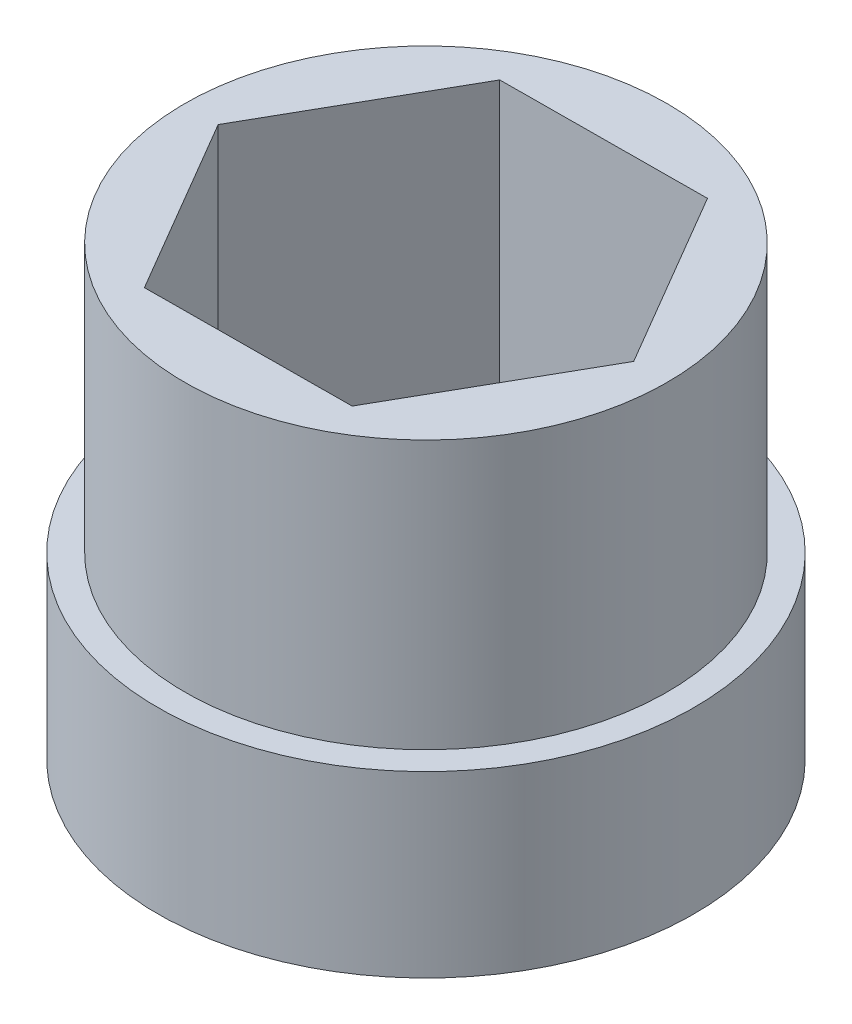
SolidWorks part; units mm, degrees
ref_plane "Front Plane" through (0, 0, 0) normal (0, 0, 1) x (1, 0, 0)
ref_plane "Top Plane" through (0, 0, 0) normal (0, 1, 0) x (1, 0, 0)
ref_plane "Right Plane" through (0, 0, 0) normal (1, 0, 0) x (0, 0, -1)
sketch "Sketch1" plane through (0, 0, 0) normal (0, 1, 0) x (1, 0, 0)
  line L1 (3.626, 6.373) -> (-3.7062, 6.3267)
  line L2 (-3.7062, 6.3267) -> (-7.3322, -0.0463)
  line L3 (-7.3322, -0.0463) -> (-3.626, -6.373)
  line L4 (-3.626, -6.373) -> (3.7062, -6.3267)
  line L5 (3.7062, -6.3267) -> (7.3322, 0.0463)
  line L6 (7.3322, 0.0463) -> (3.626, 6.373)
  circle A0 centre (0, 0) radius 8.5725
  circle A1 centre (0, 0) radius 6.35 construction
  dimension "D1" = 17.145
  dimension "D2" = 12.7
  dimension "D3" = 6.373
extrude "Boss-Extrude1" add sketch "Sketch1" along normal blind 9.525
sketch "Sketch2" plane through (0, 0, 0) normal (0, -1, 0) x (1, 0, 0)
  circle A0 centre (0, 0) radius 9.525
  dimension "D1" = 19.05
extrude "Boss-Extrude2" add sketch "Sketch2" along normal blind 3.175
sketch "Sketch3" plane through (0, -3.175, 0) normal (0, -1, 0) x (1, 0, 0)
  arc A0 (-6.7917, 0.2685) -> (-6.7919, -0.2641) centre (0, 0) ccw construction
  arc A1 (-6.5617, 1.7731) -> (-6.6804, 1.2538) centre (0, 0) ccw construction
  arc A2 (-6.0026, 3.1887) -> (-6.2339, 2.7089) centre (0, 0) ccw construction
  arc A3 (-5.1426, 4.4445) -> (-5.4748, 4.0282) centre (0, 0) ccw construction
  arc A4 (-4.0246, 5.4774) -> (-4.4412, 5.1454) centre (0, 0) ccw construction
  arc A5 (-2.7049, 6.2356) -> (-3.1848, 6.0047) centre (0, 0) ccw construction
  arc A6 (-1.2495, 6.6812) -> (-1.7688, 6.5628) centre (0, 0) ccw construction
  arc A7 (0.2685, 6.7917) -> (-0.2641, 6.7919) centre (0, 0) ccw construction
  arc A8 (1.7731, 6.5617) -> (1.2538, 6.6804) centre (0, 0) ccw construction
  arc A9 (3.1887, 6.0026) -> (2.7089, 6.2339) centre (0, 0) ccw construction
  arc A10 (4.4445, 5.1426) -> (4.0282, 5.4748) centre (0, 0) ccw construction
  arc A11 (5.4774, 4.0246) -> (5.1454, 4.4412) centre (0, 0) ccw construction
  arc A12 (6.2356, 2.7049) -> (6.0047, 3.1848) centre (0, 0) ccw construction
  arc A13 (6.6812, 1.2495) -> (6.5628, 1.7688) centre (0, 0) ccw construction
  arc A14 (6.7917, -0.2685) -> (6.7919, 0.2641) centre (0, 0) ccw construction
  arc A15 (6.5617, -1.7731) -> (6.6804, -1.2538) centre (0, 0) ccw construction
  arc A16 (6.0026, -3.1887) -> (6.2339, -2.7089) centre (0, 0) ccw construction
  arc A17 (5.1426, -4.4445) -> (5.4748, -4.0282) centre (0, 0) ccw construction
  arc A18 (4.0246, -5.4774) -> (4.4412, -5.1454) centre (0, 0) ccw construction
  arc A19 (2.7049, -6.2356) -> (3.1848, -6.0047) centre (0, 0) ccw construction
  arc A20 (1.2495, -6.6812) -> (1.7688, -6.5628) centre (0, 0) ccw construction
  arc A21 (-0.2685, -6.7917) -> (0.2641, -6.7919) centre (0, 0) ccw construction
  arc A22 (-1.7731, -6.5617) -> (-1.2538, -6.6804) centre (0, 0) ccw construction
  arc A23 (-3.1887, -6.0026) -> (-2.7089, -6.2339) centre (0, 0) ccw construction
  arc A24 (-4.4445, -5.1426) -> (-4.0282, -5.4748) centre (0, 0) ccw construction
  arc A25 (-5.4774, -4.0246) -> (-5.1454, -4.4412) centre (0, 0) ccw construction
  arc A26 (-6.2356, -2.7049) -> (-6.0047, -3.1848) centre (0, 0) ccw construction
  arc A27 (-6.6812, -1.2495) -> (-6.5628, -1.7688) centre (0, 0) ccw construction
  arc A28 (-6.7917, 0.2685) -> (-6.7919, -0.2641) centre (0, 0) ccw
  arc A29 (-6.5617, 1.7731) -> (-6.6804, 1.2538) centre (0, 0) ccw
  arc A30 (-6.0026, 3.1887) -> (-6.2339, 2.7089) centre (0, 0) ccw
  arc A31 (-5.1426, 4.4445) -> (-5.4748, 4.0282) centre (0, 0) ccw
  arc A32 (-4.0246, 5.4774) -> (-4.4412, 5.1454) centre (0, 0) ccw
  arc A33 (-2.7049, 6.2356) -> (-3.1848, 6.0047) centre (0, 0) ccw
  arc A34 (-1.2495, 6.6812) -> (-1.7688, 6.5628) centre (0, 0) ccw
  arc A35 (0.2685, 6.7917) -> (-0.2641, 6.7919) centre (0, 0) ccw
  arc A36 (1.7731, 6.5617) -> (1.2538, 6.6804) centre (0, 0) ccw
  arc A37 (3.1887, 6.0026) -> (2.7089, 6.2339) centre (0, 0) ccw
  arc A38 (4.4445, 5.1426) -> (4.0282, 5.4748) centre (0, 0) ccw
  arc A39 (5.4774, 4.0246) -> (5.1454, 4.4412) centre (0, 0) ccw
  arc A40 (6.2356, 2.7049) -> (6.0047, 3.1848) centre (0, 0) ccw
  arc A41 (6.6812, 1.2495) -> (6.5628, 1.7688) centre (0, 0) ccw
  arc A42 (6.7917, -0.2685) -> (6.7919, 0.2641) centre (0, 0) ccw
  arc A43 (6.5617, -1.7731) -> (6.6804, -1.2538) centre (0, 0) ccw
  arc A44 (6.0026, -3.1887) -> (6.2339, -2.7089) centre (0, 0) ccw
  arc A45 (5.1426, -4.4445) -> (5.4748, -4.0282) centre (0, 0) ccw
  arc A46 (4.0246, -5.4774) -> (4.4412, -5.1454) centre (0, 0) ccw
  arc A47 (2.7049, -6.2356) -> (3.1848, -6.0047) centre (0, 0) ccw
  arc A48 (1.2495, -6.6812) -> (1.7688, -6.5628) centre (0, 0) ccw
  arc A49 (-0.2685, -6.7917) -> (0.2641, -6.7919) centre (0, 0) ccw
  arc A50 (-1.7731, -6.5617) -> (-1.2538, -6.6804) centre (0, 0) ccw
  arc A51 (-3.1887, -6.0026) -> (-2.7089, -6.2339) centre (0, 0) ccw
  arc A52 (-4.4445, -5.1426) -> (-4.0282, -5.4748) centre (0, 0) ccw
  arc A53 (-5.4774, -4.0246) -> (-5.1454, -4.4412) centre (0, 0) ccw
  arc A54 (-6.2356, -2.7049) -> (-6.0047, -3.1848) centre (0, 0) ccw
  arc A55 (-6.6812, -1.2495) -> (-6.5628, -1.7688) centre (0, 0) ccw
  circle A56 centre (0, 0) radius 9.525
  spline S0 degree 3 poles (-356.0648, -2977.4642) (50.3283, -78.6152) (6.7896, 5.9187) (-6.8638, 1.1945) (-6.9283, 1.1707) (-6.9946, 1.1449) (-7.0624, 1.1168) (-7.132, 1.0865) (-7.2152, 1.0476) (-7.2802, 1.018) (-7.3234, 0.9935) (-7.3335, 0.9852) (-7.342, 0.9765) (-7.3494, 0.9667) (-7.3555, 0.9562) (-7.3617, 0.942) (-7.367, 0.9159) (-7.3704, 0.8785) (-7.3761, 0.8335) (-7.3806, 0.7883) (-7.3856, 0.7511) (-7.3862, 0.7245) (-7.3834, 0.7093) (-7.3798, 0.6976) (-7.3747, 0.6865) (-7.3684, 0.6761) (-7.3604, 0.6658) (-7.3238, 0.6323) (-7.267, 0.5889) (-7.1946, 0.5324) (-7.1336, 0.4874) (-7.0737, 0.4448) (-7.0149, 0.4048) (-6.9573, 0.3673) (5.2975, -7.2845) (66.6012, 65.4011) (317.3255, 2981.7761) knots -24.77934 -24.77934 -24.77934 -24.77934 0.072335 0.110531 0.150078 0.190978 0.23323 0.276835 0.321791 0.391759 0.40017 0.407178 0.414186 0.421194 0.428201 0.435209 0.447802 0.473901 0.5 0.526099 0.552198 0.564791 0.571799 0.578806 0.585814 0.592822 0.59983 0.608241 0.678209 0.723165 0.76677 0.809022 0.849922 0.889469 0.927665 25.779156 25.779156 25.779156 25.779156 only from (-6.6804, 1.2538) to (-6.7917, 0.2685) construction
  spline S1 degree 3 poles (-1009.6856, -2823.5811) (31.5729, -87.8433) (7.9364, 4.2595) (-6.4259, 2.6919) (-6.4941, 2.6831) (-6.5644, 2.6726) (-6.6369, 2.6603) (-6.7114, 2.6463) (-6.8012, 2.6269) (-6.8712, 2.6124) (-6.9187, 2.5982) (-6.9304, 2.5924) (-6.9406, 2.5857) (-6.95, 2.5779) (-6.9583, 2.569) (-6.9675, 2.5565) (-6.9785, 2.5322) (-6.9901, 2.4966) (-7.0057, 2.4539) (-7.0201, 2.4109) (-7.0333, 2.3758) (-7.0398, 2.3499) (-7.0404, 2.3345) (-7.0395, 2.3223) (-7.0371, 2.3103) (-7.0332, 2.2988) (-7.0277, 2.2869) (-6.9995, 2.2461) (-6.9538, 2.1912) (-6.8957, 2.12) (-6.8463, 2.0625) (-6.7973, 2.0077) (-6.7489, 1.9556) (-6.7011, 1.9062) (3.5437, -8.2807) (79.4845, 48.9412) (972.8771, 2836.4052) knots -24.77934 -24.77934 -24.77934 -24.77934 0.072335 0.110531 0.150078 0.190978 0.23323 0.276835 0.321791 0.391759 0.40017 0.407178 0.414186 0.421194 0.428201 0.435209 0.447802 0.473901 0.5 0.526099 0.552198 0.564791 0.571799 0.578806 0.585814 0.592822 0.59983 0.608241 0.678209 0.723165 0.76677 0.809022 0.849922 0.889469 0.927665 25.779156 25.779156 25.779156 25.779156 only from (-6.2339, 2.7089) to (-6.5617, 1.7731) construction
  spline S2 degree 3 poles (-1612.6766, -2528.1119) (11.2344, -92.6665) (8.6852, 2.3867) (-5.6658, 4.0543) (-5.7342, 4.0609) (-5.8052, 4.0663) (-5.8785, 4.0704) (-5.9543, 4.0734) (-6.0461, 4.0744) (-6.1176, 4.0759) (-6.1671, 4.0726) (-6.1798, 4.0695) (-6.1912, 4.0653) (-6.2021, 4.0598) (-6.2122, 4.0529) (-6.2239, 4.0428) (-6.2401, 4.0216) (-6.2593, 3.9894) (-6.284, 3.9513) (-6.3076, 3.9126) (-6.3283, 3.8813) (-6.3404, 3.8575) (-6.3444, 3.8426) (-6.3462, 3.8305) (-6.3466, 3.8183) (-6.3454, 3.8062) (-6.3426, 3.7934) (-6.3242, 3.7474) (-6.2919, 3.6836) (-6.2511, 3.6013) (-6.2157, 3.5342) (-6.1802, 3.4699) (-6.1445, 3.4084) (-6.1089, 3.3496) (1.6123, -8.8616) (88.3821, 30.0272) (1579.6446, 2548.8051) knots -24.77934 -24.77934 -24.77934 -24.77934 0.072335 0.110531 0.150078 0.190978 0.23323 0.276835 0.321791 0.391759 0.40017 0.407178 0.414186 0.421194 0.428201 0.435209 0.447802 0.473901 0.5 0.526099 0.552198 0.564791 0.571799 0.578806 0.585814 0.592822 0.59983 0.608241 0.678209 0.723165 0.76677 0.809022 0.849922 0.889469 0.927665 25.779156 25.779156 25.779156 25.779156 only from (-5.4748, 4.0282) to (-6.0026, 3.1887) construction
  spline S3 degree 3 poles (-2134.8012, -2105.8725) (-9.6675, -92.843) (8.9986, 0.3942) (-4.6216, 5.2134) (-4.6868, 5.2351) (-4.7548, 5.2561) (-4.8253, 5.2765) (-4.8986, 5.2962) (-4.9879, 5.3177) (-5.0572, 5.335) (-5.1062, 5.3428) (-5.1193, 5.3426) (-5.1314, 5.3411) (-5.1432, 5.3381) (-5.1546, 5.3336) (-5.1683, 5.3264) (-5.1887, 5.3093) (-5.2147, 5.2822) (-5.2472, 5.2506) (-5.2789, 5.2181) (-5.306, 5.1921) (-5.3231, 5.1717) (-5.3303, 5.158) (-5.3348, 5.1466) (-5.3378, 5.1348) (-5.3393, 5.1227) (-5.3395, 5.1097) (-5.3318, 5.0607) (-5.3144, 4.9913) (-5.293, 4.902) (-5.2734, 4.8287) (-5.2531, 4.7581) (-5.232, 4.6902) (-5.2104, 4.6249) (-0.4001, -8.9982) (92.8478, 9.6075) (2107.2021, 2133.3972) knots -24.77934 -24.77934 -24.77934 -24.77934 0.072335 0.110531 0.150078 0.190978 0.23323 0.276835 0.321791 0.391759 0.40017 0.407178 0.414186 0.421194 0.428201 0.435209 0.447802 0.473901 0.5 0.526099 0.552198 0.564791 0.571799 0.578806 0.585814 0.592822 0.59983 0.608241 0.678209 0.723165 0.76677 0.809022 0.849922 0.889469 0.927665 25.779156 25.779156 25.779156 25.779156 only from (-4.4412, 5.1454) to (-5.1426, 4.4445) construction
  spline S4 degree 3 poles (-2549.878, -1578.0359) (-30.0847, -88.364) (8.8607, -1.618) (-3.3456, 6.1111) (-3.4044, 6.1467) (-3.466, 6.1824) (-3.5302, 6.2179) (-3.5972, 6.2534) (-3.6795, 6.2942) (-3.7433, 6.3266) (-3.7893, 6.345) (-3.8021, 6.3478) (-3.8142, 6.349) (-3.8264, 6.3487) (-3.8385, 6.3469) (-3.8534, 6.3429) (-3.8772, 6.3308) (-3.9085, 6.3102) (-3.9473, 6.2865) (-3.9854, 6.2619) (-4.0176, 6.2426) (-4.0388, 6.2265) (-4.0489, 6.2148) (-4.0558, 6.2047) (-4.0613, 6.1938) (-4.0655, 6.1824) (-4.0686, 6.1697) (-4.072, 6.1202) (-4.0705, 6.0487) (-4.0695, 5.9569) (-4.0667, 5.8811) (-4.0626, 5.8078) (-4.0572, 5.7369) (-4.0507, 5.6684) (-2.3923, -8.6836) (92.6578, -11.294) (2529.0957, 1611.0119) knots -24.77934 -24.77934 -24.77934 -24.77934 0.072335 0.110531 0.150078 0.190978 0.23323 0.276835 0.321791 0.391759 0.40017 0.407178 0.414186 0.421194 0.428201 0.435209 0.447802 0.473901 0.5 0.526099 0.552198 0.564791 0.571799 0.578806 0.585814 0.592822 0.59983 0.608241 0.678209 0.723165 0.76677 0.809022 0.849922 0.889469 0.927665 25.779156 25.779156 25.779156 25.779156 only from (-3.1848, 6.0047) to (-4.0246, 5.4774) construction
  spline S5 degree 3 poles (-2837.0933, -971.07) (-48.9932, -79.4541) (8.2785, -3.5491) (-1.9019, 6.7024) (-1.9513, 6.7502) (-2.0033, 6.7986) (-2.0581, 6.8476) (-2.1155, 6.8971) (-2.1867, 6.9552) (-2.2416, 7.0009) (-2.2824, 7.0292) (-2.2942, 7.0347) (-2.3058, 7.0386) (-2.3178, 7.041) (-2.3299, 7.0419) (-2.3454, 7.0413) (-2.3712, 7.0348) (-2.4064, 7.0217) (-2.4494, 7.0073) (-2.4921, 6.9917) (-2.5277, 6.9801) (-2.552, 6.9691) (-2.5645, 6.96) (-2.5734, 6.9516) (-2.5813, 6.9423) (-2.5879, 6.932) (-2.5937, 6.9203) (-2.608, 6.8729) (-2.6225, 6.8029) (-2.642, 6.7131) (-2.656, 6.6386) (-2.6684, 6.5662) (-2.6789, 6.4958) (-2.6878, 6.4277) (-4.2646, -7.9335) (87.8215, -31.6291) (2824.1698, 1007.8437) knots -24.77934 -24.77934 -24.77934 -24.77934 0.072335 0.110531 0.150078 0.190978 0.23323 0.276835 0.321791 0.391759 0.40017 0.407178 0.414186 0.421194 0.428201 0.435209 0.447802 0.473901 0.5 0.526099 0.552198 0.564791 0.571799 0.578806 0.585814 0.592822 0.59983 0.608241 0.678209 0.723165 0.76677 0.809022 0.849922 0.889469 0.927665 25.779156 25.779156 25.779156 25.779156 only from (-1.7688, 6.5628) to (-2.7049, 6.2356) construction
  spline S6 degree 3 poles (-2982.0449, -315.4106) (-65.4451, -66.56) (7.2812, -5.3023) (-0.3628, 6.9575) (-0.4003, 7.0151) (-0.4403, 7.074) (-0.4828, 7.1339) (-0.5277, 7.1949) (-0.5842, 7.2674) (-0.6276, 7.3242) (-0.661, 7.3608) (-0.6713, 7.3688) (-0.6818, 7.3752) (-0.6929, 7.3802) (-0.7045, 7.3838) (-0.7198, 7.3867) (-0.7464, 7.3861) (-0.7836, 7.3811) (-0.8287, 7.3766) (-0.8738, 7.371) (-0.9111, 7.3676) (-0.9372, 7.3623) (-0.9514, 7.3561) (-0.962, 7.35) (-0.9717, 7.3426) (-0.9805, 7.3341) (-0.9887, 7.324) (-1.0133, 7.2809) (-1.043, 7.2159) (-1.0819, 7.1327) (-1.1122, 7.0632) (-1.1404, 6.9953) (-1.1663, 6.9291) (-1.1901, 6.8646) (-5.9231, -6.7856) (78.5815, -50.3783) (2977.6283, 354.1381) knots -24.77934 -24.77934 -24.77934 -24.77934 0.072335 0.110531 0.150078 0.190978 0.23323 0.276835 0.321791 0.391759 0.40017 0.407178 0.414186 0.421194 0.428201 0.435209 0.447802 0.473901 0.5 0.526099 0.552198 0.564791 0.571799 0.578806 0.585814 0.592822 0.59983 0.608241 0.678209 0.723165 0.76677 0.809022 0.849922 0.889469 0.927665 25.779156 25.779156 25.779156 25.779156 only from (-0.2641, 6.7919) to (-1.2495, 6.6812) construction
  spline S7 degree 3 poles (-2977.4642, 356.0648) (-78.6152, -50.3283) (5.9187, -6.7896) (1.1945, 6.8638) (1.1707, 6.9283) (1.1449, 6.9946) (1.1168, 7.0624) (1.0865, 7.132) (1.0476, 7.2152) (1.018, 7.2802) (0.9935, 7.3234) (0.9852, 7.3335) (0.9765, 7.342) (0.9667, 7.3494) (0.9562, 7.3555) (0.942, 7.3617) (0.9159, 7.367) (0.8785, 7.3704) (0.8335, 7.3761) (0.7883, 7.3806) (0.7511, 7.3856) (0.7245, 7.3862) (0.7093, 7.3834) (0.6976, 7.3798) (0.6865, 7.3747) (0.6761, 7.3684) (0.6658, 7.3604) (0.6323, 7.3238) (0.5889, 7.267) (0.5324, 7.1946) (0.4874, 7.1336) (0.4448, 7.0737) (0.4048, 7.0149) (0.3673, 6.9573) (-7.2845, -5.2975) (65.4011, -66.6012) (2981.7761, -317.3255) knots -24.77934 -24.77934 -24.77934 -24.77934 0.072335 0.110531 0.150078 0.190978 0.23323 0.276835 0.321791 0.391759 0.40017 0.407178 0.414186 0.421194 0.428201 0.435209 0.447802 0.473901 0.5 0.526099 0.552198 0.564791 0.571799 0.578806 0.585814 0.592822 0.59983 0.608241 0.678209 0.723165 0.76677 0.809022 0.849922 0.889469 0.927665 25.779156 25.779156 25.779156 25.779156 only from (1.2538, 6.6804) to (0.2685, 6.7917) construction
  spline S8 degree 3 poles (-2823.5811, 1009.6856) (-87.8433, -31.5729) (4.2595, -7.9364) (2.6919, 6.4259) (2.6831, 6.4941) (2.6726, 6.5644) (2.6603, 6.6369) (2.6463, 6.7114) (2.6269, 6.8012) (2.6124, 6.8712) (2.5982, 6.9187) (2.5924, 6.9304) (2.5857, 6.9406) (2.5779, 6.95) (2.569, 6.9583) (2.5565, 6.9675) (2.5322, 6.9785) (2.4966, 6.9901) (2.4539, 7.0057) (2.4109, 7.0201) (2.3758, 7.0333) (2.3499, 7.0398) (2.3345, 7.0404) (2.3223, 7.0395) (2.3103, 7.0371) (2.2988, 7.0332) (2.2869, 7.0277) (2.2461, 6.9995) (2.1912, 6.9538) (2.12, 6.8957) (2.0625, 6.8463) (2.0077, 6.7973) (1.9556, 6.7489) (1.9062, 6.7011) (-8.2807, -3.5437) (48.9412, -79.4845) (2836.4052, -972.8771) knots -24.77934 -24.77934 -24.77934 -24.77934 0.072335 0.110531 0.150078 0.190978 0.23323 0.276835 0.321791 0.391759 0.40017 0.407178 0.414186 0.421194 0.428201 0.435209 0.447802 0.473901 0.5 0.526099 0.552198 0.564791 0.571799 0.578806 0.585814 0.592822 0.59983 0.608241 0.678209 0.723165 0.76677 0.809022 0.849922 0.889469 0.927665 25.779156 25.779156 25.779156 25.779156 only from (2.7089, 6.2339) to (1.7731, 6.5617) construction
  spline S9 degree 3 poles (-2528.1119, 1612.6766) (-92.6665, -11.2344) (2.3867, -8.6852) (4.0543, 5.6658) (4.0609, 5.7342) (4.0663, 5.8052) (4.0704, 5.8785) (4.0734, 5.9543) (4.0744, 6.0461) (4.0759, 6.1176) (4.0726, 6.1671) (4.0695, 6.1798) (4.0653, 6.1912) (4.0598, 6.2021) (4.0529, 6.2122) (4.0428, 6.2239) (4.0216, 6.2401) (3.9894, 6.2593) (3.9513, 6.284) (3.9126, 6.3076) (3.8813, 6.3283) (3.8575, 6.3404) (3.8426, 6.3444) (3.8305, 6.3462) (3.8183, 6.3466) (3.8062, 6.3454) (3.7934, 6.3426) (3.7474, 6.3242) (3.6836, 6.2919) (3.6013, 6.2511) (3.5342, 6.2157) (3.4699, 6.1802) (3.4084, 6.1445) (3.3496, 6.1089) (-8.8616, -1.6123) (30.0272, -88.3821) (2548.8051, -1579.6446) knots -24.77934 -24.77934 -24.77934 -24.77934 0.072335 0.110531 0.150078 0.190978 0.23323 0.276835 0.321791 0.391759 0.40017 0.407178 0.414186 0.421194 0.428201 0.435209 0.447802 0.473901 0.5 0.526099 0.552198 0.564791 0.571799 0.578806 0.585814 0.592822 0.59983 0.608241 0.678209 0.723165 0.76677 0.809022 0.849922 0.889469 0.927665 25.779156 25.779156 25.779156 25.779156 only from (4.0282, 5.4748) to (3.1887, 6.0026) construction
  spline S10 degree 3 poles (-2105.8725, 2134.8012) (-92.843, 9.6675) (0.3942, -8.9986) (5.2134, 4.6216) (5.2351, 4.6868) (5.2561, 4.7548) (5.2765, 4.8253) (5.2962, 4.8986) (5.3177, 4.9879) (5.335, 5.0572) (5.3428, 5.1062) (5.3426, 5.1193) (5.3411, 5.1314) (5.3381, 5.1432) (5.3336, 5.1546) (5.3264, 5.1683) (5.3093, 5.1887) (5.2822, 5.2147) (5.2506, 5.2472) (5.2181, 5.2789) (5.1921, 5.306) (5.1717, 5.3231) (5.158, 5.3303) (5.1466, 5.3348) (5.1348, 5.3378) (5.1227, 5.3393) (5.1097, 5.3395) (5.0607, 5.3318) (4.9913, 5.3144) (4.902, 5.293) (4.8287, 5.2734) (4.7581, 5.2531) (4.6902, 5.232) (4.6249, 5.2104) (-8.9982, 0.4001) (9.6075, -92.8478) (2133.3972, -2107.2021) knots -24.77934 -24.77934 -24.77934 -24.77934 0.072335 0.110531 0.150078 0.190978 0.23323 0.276835 0.321791 0.391759 0.40017 0.407178 0.414186 0.421194 0.428201 0.435209 0.447802 0.473901 0.5 0.526099 0.552198 0.564791 0.571799 0.578806 0.585814 0.592822 0.59983 0.608241 0.678209 0.723165 0.76677 0.809022 0.849922 0.889469 0.927665 25.779156 25.779156 25.779156 25.779156 only from (5.1454, 4.4412) to (4.4445, 5.1426) construction
  spline S11 degree 3 poles (-1578.0359, 2549.878) (-88.364, 30.0847) (-1.618, -8.8607) (6.1111, 3.3456) (6.1467, 3.4044) (6.1824, 3.466) (6.2179, 3.5302) (6.2534, 3.5972) (6.2942, 3.6795) (6.3266, 3.7433) (6.345, 3.7893) (6.3478, 3.8021) (6.349, 3.8142) (6.3487, 3.8264) (6.3469, 3.8385) (6.3429, 3.8534) (6.3308, 3.8772) (6.3102, 3.9085) (6.2865, 3.9473) (6.2619, 3.9854) (6.2426, 4.0176) (6.2265, 4.0388) (6.2148, 4.0489) (6.2047, 4.0558) (6.1938, 4.0613) (6.1824, 4.0655) (6.1697, 4.0686) (6.1202, 4.072) (6.0487, 4.0705) (5.9569, 4.0695) (5.8811, 4.0667) (5.8078, 4.0626) (5.7369, 4.0572) (5.6684, 4.0507) (-8.6836, 2.3923) (-11.294, -92.6578) (1611.0119, -2529.0957) knots -24.77934 -24.77934 -24.77934 -24.77934 0.072335 0.110531 0.150078 0.190978 0.23323 0.276835 0.321791 0.391759 0.40017 0.407178 0.414186 0.421194 0.428201 0.435209 0.447802 0.473901 0.5 0.526099 0.552198 0.564791 0.571799 0.578806 0.585814 0.592822 0.59983 0.608241 0.678209 0.723165 0.76677 0.809022 0.849922 0.889469 0.927665 25.779156 25.779156 25.779156 25.779156 only from (6.0047, 3.1848) to (5.4774, 4.0246) construction
  spline S12 degree 3 poles (-971.07, 2837.0933) (-79.4541, 48.9932) (-3.5491, -8.2785) (6.7024, 1.9019) (6.7502, 1.9513) (6.7986, 2.0033) (6.8476, 2.0581) (6.8971, 2.1155) (6.9552, 2.1867) (7.0009, 2.2416) (7.0292, 2.2824) (7.0347, 2.2942) (7.0386, 2.3058) (7.041, 2.3178) (7.0419, 2.3299) (7.0413, 2.3454) (7.0348, 2.3712) (7.0217, 2.4064) (7.0073, 2.4494) (6.9917, 2.4921) (6.9801, 2.5277) (6.9691, 2.552) (6.96, 2.5645) (6.9516, 2.5734) (6.9423, 2.5813) (6.932, 2.5879) (6.9203, 2.5937) (6.8729, 2.608) (6.8029, 2.6225) (6.7131, 2.642) (6.6386, 2.656) (6.5662, 2.6684) (6.4958, 2.6789) (6.4277, 2.6878) (-7.9335, 4.2646) (-31.6291, -87.8215) (1007.8437, -2824.1698) knots -24.77934 -24.77934 -24.77934 -24.77934 0.072335 0.110531 0.150078 0.190978 0.23323 0.276835 0.321791 0.391759 0.40017 0.407178 0.414186 0.421194 0.428201 0.435209 0.447802 0.473901 0.5 0.526099 0.552198 0.564791 0.571799 0.578806 0.585814 0.592822 0.59983 0.608241 0.678209 0.723165 0.76677 0.809022 0.849922 0.889469 0.927665 25.779156 25.779156 25.779156 25.779156 only from (6.5628, 1.7688) to (6.2356, 2.7049) construction
  spline S13 degree 3 poles (-315.4106, 2982.0449) (-66.56, 65.4451) (-5.3023, -7.2812) (6.9575, 0.3628) (7.0151, 0.4003) (7.074, 0.4403) (7.1339, 0.4828) (7.1949, 0.5277) (7.2674, 0.5842) (7.3242, 0.6276) (7.3608, 0.661) (7.3688, 0.6713) (7.3752, 0.6818) (7.3802, 0.6929) (7.3838, 0.7045) (7.3867, 0.7198) (7.3861, 0.7464) (7.3811, 0.7836) (7.3766, 0.8287) (7.371, 0.8738) (7.3676, 0.9111) (7.3623, 0.9372) (7.3561, 0.9514) (7.35, 0.962) (7.3426, 0.9717) (7.3341, 0.9805) (7.324, 0.9887) (7.2809, 1.0133) (7.2159, 1.043) (7.1327, 1.0819) (7.0632, 1.1122) (6.9953, 1.1404) (6.9291, 1.1663) (6.8646, 1.1901) (-6.7856, 5.9231) (-50.3783, -78.5815) (354.1381, -2977.6283) knots -24.77934 -24.77934 -24.77934 -24.77934 0.072335 0.110531 0.150078 0.190978 0.23323 0.276835 0.321791 0.391759 0.40017 0.407178 0.414186 0.421194 0.428201 0.435209 0.447802 0.473901 0.5 0.526099 0.552198 0.564791 0.571799 0.578806 0.585814 0.592822 0.59983 0.608241 0.678209 0.723165 0.76677 0.809022 0.849922 0.889469 0.927665 25.779156 25.779156 25.779156 25.779156 only from (6.7919, 0.2641) to (6.6812, 1.2495) construction
  spline S14 degree 3 poles (356.0648, 2977.4642) (-50.3283, 78.6152) (-6.7896, -5.9187) (6.8638, -1.1945) (6.9283, -1.1707) (6.9946, -1.1449) (7.0624, -1.1168) (7.132, -1.0865) (7.2152, -1.0476) (7.2802, -1.018) (7.3234, -0.9935) (7.3335, -0.9852) (7.342, -0.9765) (7.3494, -0.9667) (7.3555, -0.9562) (7.3617, -0.942) (7.367, -0.9159) (7.3704, -0.8785) (7.3761, -0.8335) (7.3806, -0.7883) (7.3856, -0.7511) (7.3862, -0.7245) (7.3834, -0.7093) (7.3798, -0.6976) (7.3747, -0.6865) (7.3684, -0.6761) (7.3604, -0.6658) (7.3238, -0.6323) (7.267, -0.5889) (7.1946, -0.5324) (7.1336, -0.4874) (7.0737, -0.4448) (7.0149, -0.4048) (6.9573, -0.3673) (-5.2975, 7.2845) (-66.6012, -65.4011) (-317.3255, -2981.7761) knots -24.77934 -24.77934 -24.77934 -24.77934 0.072335 0.110531 0.150078 0.190978 0.23323 0.276835 0.321791 0.391759 0.40017 0.407178 0.414186 0.421194 0.428201 0.435209 0.447802 0.473901 0.5 0.526099 0.552198 0.564791 0.571799 0.578806 0.585814 0.592822 0.59983 0.608241 0.678209 0.723165 0.76677 0.809022 0.849922 0.889469 0.927665 25.779156 25.779156 25.779156 25.779156 only from (6.6804, -1.2538) to (6.7917, -0.2685) construction
  spline S15 degree 3 poles (1009.6856, 2823.5811) (-31.5729, 87.8433) (-7.9364, -4.2595) (6.4259, -2.6919) (6.4941, -2.6831) (6.5644, -2.6726) (6.6369, -2.6603) (6.7114, -2.6463) (6.8012, -2.6269) (6.8712, -2.6124) (6.9187, -2.5982) (6.9304, -2.5924) (6.9406, -2.5857) (6.95, -2.5779) (6.9583, -2.569) (6.9675, -2.5565) (6.9785, -2.5322) (6.9901, -2.4966) (7.0057, -2.4539) (7.0201, -2.4109) (7.0333, -2.3758) (7.0398, -2.3499) (7.0404, -2.3345) (7.0395, -2.3223) (7.0371, -2.3103) (7.0332, -2.2988) (7.0277, -2.2869) (6.9995, -2.2461) (6.9538, -2.1912) (6.8957, -2.12) (6.8463, -2.0625) (6.7973, -2.0077) (6.7489, -1.9556) (6.7011, -1.9062) (-3.5437, 8.2807) (-79.4845, -48.9412) (-972.8771, -2836.4052) knots -24.77934 -24.77934 -24.77934 -24.77934 0.072335 0.110531 0.150078 0.190978 0.23323 0.276835 0.321791 0.391759 0.40017 0.407178 0.414186 0.421194 0.428201 0.435209 0.447802 0.473901 0.5 0.526099 0.552198 0.564791 0.571799 0.578806 0.585814 0.592822 0.59983 0.608241 0.678209 0.723165 0.76677 0.809022 0.849922 0.889469 0.927665 25.779156 25.779156 25.779156 25.779156 only from (6.2339, -2.7089) to (6.5617, -1.7731) construction
  spline S16 degree 3 poles (1612.6766, 2528.1119) (-11.2344, 92.6665) (-8.6852, -2.3867) (5.6658, -4.0543) (5.7342, -4.0609) (5.8052, -4.0663) (5.8785, -4.0704) (5.9543, -4.0734) (6.0461, -4.0744) (6.1176, -4.0759) (6.1671, -4.0726) (6.1798, -4.0695) (6.1912, -4.0653) (6.2021, -4.0598) (6.2122, -4.0529) (6.2239, -4.0428) (6.2401, -4.0216) (6.2593, -3.9894) (6.284, -3.9513) (6.3076, -3.9126) (6.3283, -3.8813) (6.3404, -3.8575) (6.3444, -3.8426) (6.3462, -3.8305) (6.3466, -3.8183) (6.3454, -3.8062) (6.3426, -3.7934) (6.3242, -3.7474) (6.2919, -3.6836) (6.2511, -3.6013) (6.2157, -3.5342) (6.1802, -3.4699) (6.1445, -3.4084) (6.1089, -3.3496) (-1.6123, 8.8616) (-88.3821, -30.0272) (-1579.6446, -2548.8051) knots -24.77934 -24.77934 -24.77934 -24.77934 0.072335 0.110531 0.150078 0.190978 0.23323 0.276835 0.321791 0.391759 0.40017 0.407178 0.414186 0.421194 0.428201 0.435209 0.447802 0.473901 0.5 0.526099 0.552198 0.564791 0.571799 0.578806 0.585814 0.592822 0.59983 0.608241 0.678209 0.723165 0.76677 0.809022 0.849922 0.889469 0.927665 25.779156 25.779156 25.779156 25.779156 only from (5.4748, -4.0282) to (6.0026, -3.1887) construction
  spline S17 degree 3 poles (2134.8012, 2105.8725) (9.6675, 92.843) (-8.9986, -0.3942) (4.6216, -5.2134) (4.6868, -5.2351) (4.7548, -5.2561) (4.8253, -5.2765) (4.8986, -5.2962) (4.9879, -5.3177) (5.0572, -5.335) (5.1062, -5.3428) (5.1193, -5.3426) (5.1314, -5.3411) (5.1432, -5.3381) (5.1546, -5.3336) (5.1683, -5.3264) (5.1887, -5.3093) (5.2147, -5.2822) (5.2472, -5.2506) (5.2789, -5.2181) (5.306, -5.1921) (5.3231, -5.1717) (5.3303, -5.158) (5.3348, -5.1466) (5.3378, -5.1348) (5.3393, -5.1227) (5.3395, -5.1097) (5.3318, -5.0607) (5.3144, -4.9913) (5.293, -4.902) (5.2734, -4.8287) (5.2531, -4.7581) (5.232, -4.6902) (5.2104, -4.6249) (0.4001, 8.9982) (-92.8478, -9.6075) (-2107.2021, -2133.3972) knots -24.77934 -24.77934 -24.77934 -24.77934 0.072335 0.110531 0.150078 0.190978 0.23323 0.276835 0.321791 0.391759 0.40017 0.407178 0.414186 0.421194 0.428201 0.435209 0.447802 0.473901 0.5 0.526099 0.552198 0.564791 0.571799 0.578806 0.585814 0.592822 0.59983 0.608241 0.678209 0.723165 0.76677 0.809022 0.849922 0.889469 0.927665 25.779156 25.779156 25.779156 25.779156 only from (4.4412, -5.1454) to (5.1426, -4.4445) construction
  spline S18 degree 3 poles (2549.878, 1578.0359) (30.0847, 88.364) (-8.8607, 1.618) (3.3456, -6.1111) (3.4044, -6.1467) (3.466, -6.1824) (3.5302, -6.2179) (3.5972, -6.2534) (3.6795, -6.2942) (3.7433, -6.3266) (3.7893, -6.345) (3.8021, -6.3478) (3.8142, -6.349) (3.8264, -6.3487) (3.8385, -6.3469) (3.8534, -6.3429) (3.8772, -6.3308) (3.9085, -6.3102) (3.9473, -6.2865) (3.9854, -6.2619) (4.0176, -6.2426) (4.0388, -6.2265) (4.0489, -6.2148) (4.0558, -6.2047) (4.0613, -6.1938) (4.0655, -6.1824) (4.0686, -6.1697) (4.072, -6.1202) (4.0705, -6.0487) (4.0695, -5.9569) (4.0667, -5.8811) (4.0626, -5.8078) (4.0572, -5.7369) (4.0507, -5.6684) (2.3923, 8.6836) (-92.6578, 11.294) (-2529.0957, -1611.0119) knots -24.77934 -24.77934 -24.77934 -24.77934 0.072335 0.110531 0.150078 0.190978 0.23323 0.276835 0.321791 0.391759 0.40017 0.407178 0.414186 0.421194 0.428201 0.435209 0.447802 0.473901 0.5 0.526099 0.552198 0.564791 0.571799 0.578806 0.585814 0.592822 0.59983 0.608241 0.678209 0.723165 0.76677 0.809022 0.849922 0.889469 0.927665 25.779156 25.779156 25.779156 25.779156 only from (3.1848, -6.0047) to (4.0246, -5.4774) construction
  spline S19 degree 3 poles (2837.0933, 971.07) (48.9932, 79.4541) (-8.2785, 3.5491) (1.9019, -6.7024) (1.9513, -6.7502) (2.0033, -6.7986) (2.0581, -6.8476) (2.1155, -6.8971) (2.1867, -6.9552) (2.2416, -7.0009) (2.2824, -7.0292) (2.2942, -7.0347) (2.3058, -7.0386) (2.3178, -7.041) (2.3299, -7.0419) (2.3454, -7.0413) (2.3712, -7.0348) (2.4064, -7.0217) (2.4494, -7.0073) (2.4921, -6.9917) (2.5277, -6.9801) (2.552, -6.9691) (2.5645, -6.96) (2.5734, -6.9516) (2.5813, -6.9423) (2.5879, -6.932) (2.5937, -6.9203) (2.608, -6.8729) (2.6225, -6.8029) (2.642, -6.7131) (2.656, -6.6386) (2.6684, -6.5662) (2.6789, -6.4958) (2.6878, -6.4277) (4.2646, 7.9335) (-87.8215, 31.6291) (-2824.1698, -1007.8437) knots -24.77934 -24.77934 -24.77934 -24.77934 0.072335 0.110531 0.150078 0.190978 0.23323 0.276835 0.321791 0.391759 0.40017 0.407178 0.414186 0.421194 0.428201 0.435209 0.447802 0.473901 0.5 0.526099 0.552198 0.564791 0.571799 0.578806 0.585814 0.592822 0.59983 0.608241 0.678209 0.723165 0.76677 0.809022 0.849922 0.889469 0.927665 25.779156 25.779156 25.779156 25.779156 only from (1.7688, -6.5628) to (2.7049, -6.2356) construction
  spline S20 degree 3 poles (2982.0449, 315.4106) (65.4451, 66.56) (-7.2812, 5.3023) (0.3628, -6.9575) (0.4003, -7.0151) (0.4403, -7.074) (0.4828, -7.1339) (0.5277, -7.1949) (0.5842, -7.2674) (0.6276, -7.3242) (0.661, -7.3608) (0.6713, -7.3688) (0.6818, -7.3752) (0.6929, -7.3802) (0.7045, -7.3838) (0.7198, -7.3867) (0.7464, -7.3861) (0.7836, -7.3811) (0.8287, -7.3766) (0.8738, -7.371) (0.9111, -7.3676) (0.9372, -7.3623) (0.9514, -7.3561) (0.962, -7.35) (0.9717, -7.3426) (0.9805, -7.3341) (0.9887, -7.324) (1.0133, -7.2809) (1.043, -7.2159) (1.0819, -7.1327) (1.1122, -7.0632) (1.1404, -6.9953) (1.1663, -6.9291) (1.1901, -6.8646) (5.9231, 6.7856) (-78.5815, 50.3783) (-2977.6283, -354.1381) knots -24.77934 -24.77934 -24.77934 -24.77934 0.072335 0.110531 0.150078 0.190978 0.23323 0.276835 0.321791 0.391759 0.40017 0.407178 0.414186 0.421194 0.428201 0.435209 0.447802 0.473901 0.5 0.526099 0.552198 0.564791 0.571799 0.578806 0.585814 0.592822 0.59983 0.608241 0.678209 0.723165 0.76677 0.809022 0.849922 0.889469 0.927665 25.779156 25.779156 25.779156 25.779156 only from (0.2641, -6.7919) to (1.2495, -6.6812) construction
  spline S21 degree 3 poles (2977.4642, -356.0648) (78.6152, 50.3283) (-5.9187, 6.7896) (-1.1945, -6.8638) (-1.1707, -6.9283) (-1.1449, -6.9946) (-1.1168, -7.0624) (-1.0865, -7.132) (-1.0476, -7.2152) (-1.018, -7.2802) (-0.9935, -7.3234) (-0.9852, -7.3335) (-0.9765, -7.342) (-0.9667, -7.3494) (-0.9562, -7.3555) (-0.942, -7.3617) (-0.9159, -7.367) (-0.8785, -7.3704) (-0.8335, -7.3761) (-0.7883, -7.3806) (-0.7511, -7.3856) (-0.7245, -7.3862) (-0.7093, -7.3834) (-0.6976, -7.3798) (-0.6865, -7.3747) (-0.6761, -7.3684) (-0.6658, -7.3604) (-0.6323, -7.3238) (-0.5889, -7.267) (-0.5324, -7.1946) (-0.4874, -7.1336) (-0.4448, -7.0737) (-0.4048, -7.0149) (-0.3673, -6.9573) (7.2845, 5.2975) (-65.4011, 66.6012) (-2981.7761, 317.3255) knots -24.77934 -24.77934 -24.77934 -24.77934 0.072335 0.110531 0.150078 0.190978 0.23323 0.276835 0.321791 0.391759 0.40017 0.407178 0.414186 0.421194 0.428201 0.435209 0.447802 0.473901 0.5 0.526099 0.552198 0.564791 0.571799 0.578806 0.585814 0.592822 0.59983 0.608241 0.678209 0.723165 0.76677 0.809022 0.849922 0.889469 0.927665 25.779156 25.779156 25.779156 25.779156 only from (-1.2538, -6.6804) to (-0.2685, -6.7917) construction
  spline S22 degree 3 poles (2823.5811, -1009.6856) (87.8433, 31.5729) (-4.2595, 7.9364) (-2.6919, -6.4259) (-2.6831, -6.4941) (-2.6726, -6.5644) (-2.6603, -6.6369) (-2.6463, -6.7114) (-2.6269, -6.8012) (-2.6124, -6.8712) (-2.5982, -6.9187) (-2.5924, -6.9304) (-2.5857, -6.9406) (-2.5779, -6.95) (-2.569, -6.9583) (-2.5565, -6.9675) (-2.5322, -6.9785) (-2.4966, -6.9901) (-2.4539, -7.0057) (-2.4109, -7.0201) (-2.3758, -7.0333) (-2.3499, -7.0398) (-2.3345, -7.0404) (-2.3223, -7.0395) (-2.3103, -7.0371) (-2.2988, -7.0332) (-2.2869, -7.0277) (-2.2461, -6.9995) (-2.1912, -6.9538) (-2.12, -6.8957) (-2.0625, -6.8463) (-2.0077, -6.7973) (-1.9556, -6.7489) (-1.9062, -6.7011) (8.2807, 3.5437) (-48.9412, 79.4845) (-2836.4052, 972.8771) knots -24.77934 -24.77934 -24.77934 -24.77934 0.072335 0.110531 0.150078 0.190978 0.23323 0.276835 0.321791 0.391759 0.40017 0.407178 0.414186 0.421194 0.428201 0.435209 0.447802 0.473901 0.5 0.526099 0.552198 0.564791 0.571799 0.578806 0.585814 0.592822 0.59983 0.608241 0.678209 0.723165 0.76677 0.809022 0.849922 0.889469 0.927665 25.779156 25.779156 25.779156 25.779156 only from (-2.7089, -6.2339) to (-1.7731, -6.5617) construction
  spline S23 degree 3 poles (2528.1119, -1612.6766) (92.6665, 11.2344) (-2.3867, 8.6852) (-4.0543, -5.6658) (-4.0609, -5.7342) (-4.0663, -5.8052) (-4.0704, -5.8785) (-4.0734, -5.9543) (-4.0744, -6.0461) (-4.0759, -6.1176) (-4.0726, -6.1671) (-4.0695, -6.1798) (-4.0653, -6.1912) (-4.0598, -6.2021) (-4.0529, -6.2122) (-4.0428, -6.2239) (-4.0216, -6.2401) (-3.9894, -6.2593) (-3.9513, -6.284) (-3.9126, -6.3076) (-3.8813, -6.3283) (-3.8575, -6.3404) (-3.8426, -6.3444) (-3.8305, -6.3462) (-3.8183, -6.3466) (-3.8062, -6.3454) (-3.7934, -6.3426) (-3.7474, -6.3242) (-3.6836, -6.2919) (-3.6013, -6.2511) (-3.5342, -6.2157) (-3.4699, -6.1802) (-3.4084, -6.1445) (-3.3496, -6.1089) (8.8616, 1.6123) (-30.0272, 88.3821) (-2548.8051, 1579.6446) knots -24.77934 -24.77934 -24.77934 -24.77934 0.072335 0.110531 0.150078 0.190978 0.23323 0.276835 0.321791 0.391759 0.40017 0.407178 0.414186 0.421194 0.428201 0.435209 0.447802 0.473901 0.5 0.526099 0.552198 0.564791 0.571799 0.578806 0.585814 0.592822 0.59983 0.608241 0.678209 0.723165 0.76677 0.809022 0.849922 0.889469 0.927665 25.779156 25.779156 25.779156 25.779156 only from (-4.0282, -5.4748) to (-3.1887, -6.0026) construction
  spline S24 degree 3 poles (2105.8725, -2134.8012) (92.843, -9.6675) (-0.3942, 8.9986) (-5.2134, -4.6216) (-5.2351, -4.6868) (-5.2561, -4.7548) (-5.2765, -4.8253) (-5.2962, -4.8986) (-5.3177, -4.9879) (-5.335, -5.0572) (-5.3428, -5.1062) (-5.3426, -5.1193) (-5.3411, -5.1314) (-5.3381, -5.1432) (-5.3336, -5.1546) (-5.3264, -5.1683) (-5.3093, -5.1887) (-5.2822, -5.2147) (-5.2506, -5.2472) (-5.2181, -5.2789) (-5.1921, -5.306) (-5.1717, -5.3231) (-5.158, -5.3303) (-5.1466, -5.3348) (-5.1348, -5.3378) (-5.1227, -5.3393) (-5.1097, -5.3395) (-5.0607, -5.3318) (-4.9913, -5.3144) (-4.902, -5.293) (-4.8287, -5.2734) (-4.7581, -5.2531) (-4.6902, -5.232) (-4.6249, -5.2104) (8.9982, -0.4001) (-9.6075, 92.8478) (-2133.3972, 2107.2021) knots -24.77934 -24.77934 -24.77934 -24.77934 0.072335 0.110531 0.150078 0.190978 0.23323 0.276835 0.321791 0.391759 0.40017 0.407178 0.414186 0.421194 0.428201 0.435209 0.447802 0.473901 0.5 0.526099 0.552198 0.564791 0.571799 0.578806 0.585814 0.592822 0.59983 0.608241 0.678209 0.723165 0.76677 0.809022 0.849922 0.889469 0.927665 25.779156 25.779156 25.779156 25.779156 only from (-5.1454, -4.4412) to (-4.4445, -5.1426) construction
  spline S25 degree 3 poles (1578.0359, -2549.878) (88.364, -30.0847) (1.618, 8.8607) (-6.1111, -3.3456) (-6.1467, -3.4044) (-6.1824, -3.466) (-6.2179, -3.5302) (-6.2534, -3.5972) (-6.2942, -3.6795) (-6.3266, -3.7433) (-6.345, -3.7893) (-6.3478, -3.8021) (-6.349, -3.8142) (-6.3487, -3.8264) (-6.3469, -3.8385) (-6.3429, -3.8534) (-6.3308, -3.8772) (-6.3102, -3.9085) (-6.2865, -3.9473) (-6.2619, -3.9854) (-6.2426, -4.0176) (-6.2265, -4.0388) (-6.2148, -4.0489) (-6.2047, -4.0558) (-6.1938, -4.0613) (-6.1824, -4.0655) (-6.1697, -4.0686) (-6.1202, -4.072) (-6.0487, -4.0705) (-5.9569, -4.0695) (-5.8811, -4.0667) (-5.8078, -4.0626) (-5.7369, -4.0572) (-5.6684, -4.0507) (8.6836, -2.3923) (11.294, 92.6578) (-1611.0119, 2529.0957) knots -24.77934 -24.77934 -24.77934 -24.77934 0.072335 0.110531 0.150078 0.190978 0.23323 0.276835 0.321791 0.391759 0.40017 0.407178 0.414186 0.421194 0.428201 0.435209 0.447802 0.473901 0.5 0.526099 0.552198 0.564791 0.571799 0.578806 0.585814 0.592822 0.59983 0.608241 0.678209 0.723165 0.76677 0.809022 0.849922 0.889469 0.927665 25.779156 25.779156 25.779156 25.779156 only from (-6.0047, -3.1848) to (-5.4774, -4.0246) construction
  spline S26 degree 3 poles (971.07, -2837.0933) (79.4541, -48.9932) (3.5491, 8.2785) (-6.7024, -1.9019) (-6.7502, -1.9513) (-6.7986, -2.0033) (-6.8476, -2.0581) (-6.8971, -2.1155) (-6.9552, -2.1867) (-7.0009, -2.2416) (-7.0292, -2.2824) (-7.0347, -2.2942) (-7.0386, -2.3058) (-7.041, -2.3178) (-7.0419, -2.3299) (-7.0413, -2.3454) (-7.0348, -2.3712) (-7.0217, -2.4064) (-7.0073, -2.4494) (-6.9917, -2.4921) (-6.9801, -2.5277) (-6.9691, -2.552) (-6.96, -2.5645) (-6.9516, -2.5734) (-6.9423, -2.5813) (-6.932, -2.5879) (-6.9203, -2.5937) (-6.8729, -2.608) (-6.8029, -2.6225) (-6.7131, -2.642) (-6.6386, -2.656) (-6.5662, -2.6684) (-6.4958, -2.6789) (-6.4277, -2.6878) (7.9335, -4.2646) (31.6291, 87.8215) (-1007.8437, 2824.1698) knots -24.77934 -24.77934 -24.77934 -24.77934 0.072335 0.110531 0.150078 0.190978 0.23323 0.276835 0.321791 0.391759 0.40017 0.407178 0.414186 0.421194 0.428201 0.435209 0.447802 0.473901 0.5 0.526099 0.552198 0.564791 0.571799 0.578806 0.585814 0.592822 0.59983 0.608241 0.678209 0.723165 0.76677 0.809022 0.849922 0.889469 0.927665 25.779156 25.779156 25.779156 25.779156 only from (-6.5628, -1.7688) to (-6.2356, -2.7049) construction
  spline S27 degree 3 poles (315.4106, -2982.0449) (66.56, -65.4451) (5.3023, 7.2812) (-6.9575, -0.3628) (-7.0151, -0.4003) (-7.074, -0.4403) (-7.1339, -0.4828) (-7.1949, -0.5277) (-7.2674, -0.5842) (-7.3242, -0.6276) (-7.3608, -0.661) (-7.3688, -0.6713) (-7.3752, -0.6818) (-7.3802, -0.6929) (-7.3838, -0.7045) (-7.3867, -0.7198) (-7.3861, -0.7464) (-7.3811, -0.7836) (-7.3766, -0.8287) (-7.371, -0.8738) (-7.3676, -0.9111) (-7.3623, -0.9372) (-7.3561, -0.9514) (-7.35, -0.962) (-7.3426, -0.9717) (-7.3341, -0.9805) (-7.324, -0.9887) (-7.2809, -1.0133) (-7.2159, -1.043) (-7.1327, -1.0819) (-7.0632, -1.1122) (-6.9953, -1.1404) (-6.9291, -1.1663) (-6.8646, -1.1901) (6.7856, -5.9231) (50.3783, 78.5815) (-354.1381, 2977.6283) knots -24.77934 -24.77934 -24.77934 -24.77934 0.072335 0.110531 0.150078 0.190978 0.23323 0.276835 0.321791 0.391759 0.40017 0.407178 0.414186 0.421194 0.428201 0.435209 0.447802 0.473901 0.5 0.526099 0.552198 0.564791 0.571799 0.578806 0.585814 0.592822 0.59983 0.608241 0.678209 0.723165 0.76677 0.809022 0.849922 0.889469 0.927665 25.779156 25.779156 25.779156 25.779156 only from (-6.7919, -0.2641) to (-6.6812, -1.2495) construction
  spline S28 degree 3 poles (-6.6804, 1.2538) (-6.7206, 1.2421) (-6.7817, 1.2229) (-6.8638, 1.1945) (-6.9283, 1.1707) (-6.9946, 1.1449) (-7.0624, 1.1168) (-7.132, 1.0865) (-7.2152, 1.0476) (-7.2802, 1.018) (-7.3234, 0.9935) (-7.3335, 0.9852) (-7.342, 0.9765) (-7.3494, 0.9667) (-7.3555, 0.9562) (-7.3617, 0.942) (-7.367, 0.9159) (-7.3704, 0.8785) (-7.3761, 0.8335) (-7.3806, 0.7883) (-7.3856, 0.7511) (-7.3862, 0.7245) (-7.3834, 0.7093) (-7.3798, 0.6976) (-7.3747, 0.6865) (-7.3684, 0.6761) (-7.3604, 0.6658) (-7.3238, 0.6323) (-7.267, 0.5889) (-7.1946, 0.5324) (-7.1336, 0.4874) (-7.0737, 0.4448) (-7.0149, 0.4048) (-6.9573, 0.3673) (-6.8835, 0.3212) (-6.8283, 0.2889) (-6.7917, 0.2685) knots 0.000063 0.000063 0.000063 0.000063 0.072335 0.110531 0.150078 0.190978 0.23323 0.276835 0.321791 0.391759 0.40017 0.407178 0.414186 0.421194 0.428201 0.435209 0.447802 0.473901 0.5 0.526099 0.552198 0.564791 0.571799 0.578806 0.585814 0.592822 0.59983 0.608241 0.678209 0.723165 0.76677 0.809022 0.849922 0.889469 0.927665 0.999937 0.999937 0.999937 0.999937
  spline S29 degree 3 poles (-6.2339, 2.7089) (-6.2757, 2.7064) (-6.3395, 2.7013) (-6.4259, 2.6919) (-6.4941, 2.6831) (-6.5644, 2.6726) (-6.6369, 2.6603) (-6.7114, 2.6463) (-6.8012, 2.6269) (-6.8712, 2.6124) (-6.9187, 2.5982) (-6.9304, 2.5924) (-6.9406, 2.5857) (-6.95, 2.5779) (-6.9583, 2.569) (-6.9675, 2.5565) (-6.9785, 2.5322) (-6.9901, 2.4966) (-7.0057, 2.4539) (-7.0201, 2.4109) (-7.0333, 2.3758) (-7.0398, 2.3499) (-7.0404, 2.3345) (-7.0395, 2.3223) (-7.0371, 2.3103) (-7.0332, 2.2988) (-7.0277, 2.2869) (-6.9995, 2.2461) (-6.9538, 2.1912) (-6.8957, 2.12) (-6.8463, 2.0625) (-6.7973, 2.0077) (-6.7489, 1.9556) (-6.7011, 1.9062) (-6.6395, 1.8449) (-6.5928, 1.8011) (-6.5617, 1.7731) knots 0.000063 0.000063 0.000063 0.000063 0.072335 0.110531 0.150078 0.190978 0.23323 0.276835 0.321791 0.391759 0.40017 0.407178 0.414186 0.421194 0.428201 0.435209 0.447802 0.473901 0.5 0.526099 0.552198 0.564791 0.571799 0.578806 0.585814 0.592822 0.59983 0.608241 0.678209 0.723165 0.76677 0.809022 0.849922 0.889469 0.927665 0.999937 0.999937 0.999937 0.999937
  spline S30 degree 3 poles (-5.4748, 4.0282) (-5.5161, 4.035) (-5.5794, 4.0443) (-5.6658, 4.0543) (-5.7342, 4.0609) (-5.8052, 4.0663) (-5.8785, 4.0704) (-5.9543, 4.0734) (-6.0461, 4.0744) (-6.1176, 4.0759) (-6.1671, 4.0726) (-6.1798, 4.0695) (-6.1912, 4.0653) (-6.2021, 4.0598) (-6.2122, 4.0529) (-6.2239, 4.0428) (-6.2401, 4.0216) (-6.2593, 3.9894) (-6.284, 3.9513) (-6.3076, 3.9126) (-6.3283, 3.8813) (-6.3404, 3.8575) (-6.3444, 3.8426) (-6.3462, 3.8305) (-6.3466, 3.8183) (-6.3454, 3.8062) (-6.3426, 3.7934) (-6.3242, 3.7474) (-6.2919, 3.6836) (-6.2511, 3.6013) (-6.2157, 3.5342) (-6.1802, 3.4699) (-6.1445, 3.4084) (-6.1089, 3.3496) (-6.0625, 3.2761) (-6.0267, 3.223) (-6.0026, 3.1887) knots 0.000063 0.000063 0.000063 0.000063 0.072335 0.110531 0.150078 0.190978 0.23323 0.276835 0.321791 0.391759 0.40017 0.407178 0.414186 0.421194 0.428201 0.435209 0.447802 0.473901 0.5 0.526099 0.552198 0.564791 0.571799 0.578806 0.585814 0.592822 0.59983 0.608241 0.678209 0.723165 0.76677 0.809022 0.849922 0.889469 0.927665 0.999937 0.999937 0.999937 0.999937
  spline S31 degree 3 poles (-4.4412, 5.1454) (-4.4799, 5.1613) (-4.5396, 5.1844) (-4.6216, 5.2134) (-4.6868, 5.2351) (-4.7548, 5.2561) (-4.8253, 5.2765) (-4.8986, 5.2962) (-4.9879, 5.3177) (-5.0572, 5.335) (-5.1062, 5.3428) (-5.1193, 5.3426) (-5.1314, 5.3411) (-5.1432, 5.3381) (-5.1546, 5.3336) (-5.1683, 5.3264) (-5.1887, 5.3093) (-5.2147, 5.2822) (-5.2472, 5.2506) (-5.2789, 5.2181) (-5.306, 5.1921) (-5.3231, 5.1717) (-5.3303, 5.158) (-5.3348, 5.1466) (-5.3378, 5.1348) (-5.3393, 5.1227) (-5.3395, 5.1097) (-5.3318, 5.0607) (-5.3144, 4.9913) (-5.293, 4.902) (-5.2734, 4.8287) (-5.2531, 4.7581) (-5.232, 4.6902) (-5.2104, 4.6249) (-5.1815, 4.543) (-5.1584, 4.4832) (-5.1426, 4.4445) knots 0.000063 0.000063 0.000063 0.000063 0.072335 0.110531 0.150078 0.190978 0.23323 0.276835 0.321791 0.391759 0.40017 0.407178 0.414186 0.421194 0.428201 0.435209 0.447802 0.473901 0.5 0.526099 0.552198 0.564791 0.571799 0.578806 0.585814 0.592822 0.59983 0.608241 0.678209 0.723165 0.76677 0.809022 0.849922 0.889469 0.927665 0.999937 0.999937 0.999937 0.999937
  spline S32 degree 3 poles (-3.1848, 6.0047) (-3.2191, 6.0288) (-3.2722, 6.0646) (-3.3456, 6.1111) (-3.4044, 6.1467) (-3.466, 6.1824) (-3.5302, 6.2179) (-3.5972, 6.2534) (-3.6795, 6.2942) (-3.7433, 6.3266) (-3.7893, 6.345) (-3.8021, 6.3478) (-3.8142, 6.349) (-3.8264, 6.3487) (-3.8385, 6.3469) (-3.8534, 6.3429) (-3.8772, 6.3308) (-3.9085, 6.3102) (-3.9473, 6.2865) (-3.9854, 6.2619) (-4.0176, 6.2426) (-4.0388, 6.2265) (-4.0489, 6.2148) (-4.0558, 6.2047) (-4.0613, 6.1938) (-4.0655, 6.1824) (-4.0686, 6.1697) (-4.072, 6.1202) (-4.0705, 6.0487) (-4.0695, 5.9569) (-4.0667, 5.8811) (-4.0626, 5.8078) (-4.0572, 5.7369) (-4.0507, 5.6684) (-4.0407, 5.5821) (-4.0315, 5.5187) (-4.0246, 5.4774) knots 0.000063 0.000063 0.000063 0.000063 0.072335 0.110531 0.150078 0.190978 0.23323 0.276835 0.321791 0.391759 0.40017 0.407178 0.414186 0.421194 0.428201 0.435209 0.447802 0.473901 0.5 0.526099 0.552198 0.564791 0.571799 0.578806 0.585814 0.592822 0.59983 0.608241 0.678209 0.723165 0.76677 0.809022 0.849922 0.889469 0.927665 0.999937 0.999937 0.999937 0.999937
  spline S33 degree 3 poles (-1.7688, 6.5628) (-1.7968, 6.5939) (-1.8406, 6.6407) (-1.9019, 6.7024) (-1.9513, 6.7502) (-2.0033, 6.7986) (-2.0581, 6.8476) (-2.1155, 6.8971) (-2.1867, 6.9552) (-2.2416, 7.0009) (-2.2824, 7.0292) (-2.2942, 7.0347) (-2.3058, 7.0386) (-2.3178, 7.041) (-2.3299, 7.0419) (-2.3454, 7.0413) (-2.3712, 7.0348) (-2.4064, 7.0217) (-2.4494, 7.0073) (-2.4921, 6.9917) (-2.5277, 6.9801) (-2.552, 6.9691) (-2.5645, 6.96) (-2.5734, 6.9516) (-2.5813, 6.9423) (-2.5879, 6.932) (-2.5937, 6.9203) (-2.608, 6.8729) (-2.6225, 6.8029) (-2.642, 6.7131) (-2.656, 6.6386) (-2.6684, 6.5662) (-2.6789, 6.4958) (-2.6878, 6.4277) (-2.6972, 6.3412) (-2.7024, 6.2774) (-2.7049, 6.2356) knots 0.000063 0.000063 0.000063 0.000063 0.072335 0.110531 0.150078 0.190978 0.23323 0.276835 0.321791 0.391759 0.40017 0.407178 0.414186 0.421194 0.428201 0.435209 0.447802 0.473901 0.5 0.526099 0.552198 0.564791 0.571799 0.578806 0.585814 0.592822 0.59983 0.608241 0.678209 0.723165 0.76677 0.809022 0.849922 0.889469 0.927665 0.999937 0.999937 0.999937 0.999937
  spline S34 degree 3 poles (-0.2641, 6.7919) (-0.2845, 6.8285) (-0.3168, 6.8837) (-0.3628, 6.9575) (-0.4003, 7.0151) (-0.4403, 7.074) (-0.4828, 7.1339) (-0.5277, 7.1949) (-0.5842, 7.2674) (-0.6276, 7.3242) (-0.661, 7.3608) (-0.6713, 7.3688) (-0.6818, 7.3752) (-0.6929, 7.3802) (-0.7045, 7.3838) (-0.7198, 7.3867) (-0.7464, 7.3861) (-0.7836, 7.3811) (-0.8287, 7.3766) (-0.8738, 7.371) (-0.9111, 7.3676) (-0.9372, 7.3623) (-0.9514, 7.3561) (-0.962, 7.35) (-0.9717, 7.3426) (-0.9805, 7.3341) (-0.9887, 7.324) (-1.0133, 7.2809) (-1.043, 7.2159) (-1.0819, 7.1327) (-1.1122, 7.0632) (-1.1404, 6.9953) (-1.1663, 6.9291) (-1.1901, 6.8646) (-1.2186, 6.7824) (-1.2378, 6.7214) (-1.2495, 6.6812) knots 0.000063 0.000063 0.000063 0.000063 0.072335 0.110531 0.150078 0.190978 0.23323 0.276835 0.321791 0.391759 0.40017 0.407178 0.414186 0.421194 0.428201 0.435209 0.447802 0.473901 0.5 0.526099 0.552198 0.564791 0.571799 0.578806 0.585814 0.592822 0.59983 0.608241 0.678209 0.723165 0.76677 0.809022 0.849922 0.889469 0.927665 0.999937 0.999937 0.999937 0.999937
  spline S35 degree 3 poles (1.2538, 6.6804) (1.2421, 6.7206) (1.2229, 6.7817) (1.1945, 6.8638) (1.1707, 6.9283) (1.1449, 6.9946) (1.1168, 7.0624) (1.0865, 7.132) (1.0476, 7.2152) (1.018, 7.2802) (0.9935, 7.3234) (0.9852, 7.3335) (0.9765, 7.342) (0.9667, 7.3494) (0.9562, 7.3555) (0.942, 7.3617) (0.9159, 7.367) (0.8785, 7.3704) (0.8335, 7.3761) (0.7883, 7.3806) (0.7511, 7.3856) (0.7245, 7.3862) (0.7093, 7.3834) (0.6976, 7.3798) (0.6865, 7.3747) (0.6761, 7.3684) (0.6658, 7.3604) (0.6323, 7.3238) (0.5889, 7.267) (0.5324, 7.1946) (0.4874, 7.1336) (0.4448, 7.0737) (0.4048, 7.0149) (0.3673, 6.9573) (0.3212, 6.8835) (0.2889, 6.8283) (0.2685, 6.7917) knots 0.000063 0.000063 0.000063 0.000063 0.072335 0.110531 0.150078 0.190978 0.23323 0.276835 0.321791 0.391759 0.40017 0.407178 0.414186 0.421194 0.428201 0.435209 0.447802 0.473901 0.5 0.526099 0.552198 0.564791 0.571799 0.578806 0.585814 0.592822 0.59983 0.608241 0.678209 0.723165 0.76677 0.809022 0.849922 0.889469 0.927665 0.999937 0.999937 0.999937 0.999937
  spline S36 degree 3 poles (2.7089, 6.2339) (2.7064, 6.2757) (2.7013, 6.3395) (2.6919, 6.4259) (2.6831, 6.4941) (2.6726, 6.5644) (2.6603, 6.6369) (2.6463, 6.7114) (2.6269, 6.8012) (2.6124, 6.8712) (2.5982, 6.9187) (2.5924, 6.9304) (2.5857, 6.9406) (2.5779, 6.95) (2.569, 6.9583) (2.5565, 6.9675) (2.5322, 6.9785) (2.4966, 6.9901) (2.4539, 7.0057) (2.4109, 7.0201) (2.3758, 7.0333) (2.3499, 7.0398) (2.3345, 7.0404) (2.3223, 7.0395) (2.3103, 7.0371) (2.2988, 7.0332) (2.2869, 7.0277) (2.2461, 6.9995) (2.1912, 6.9538) (2.12, 6.8957) (2.0625, 6.8463) (2.0077, 6.7973) (1.9556, 6.7489) (1.9062, 6.7011) (1.8449, 6.6395) (1.8011, 6.5928) (1.7731, 6.5617) knots 0.000063 0.000063 0.000063 0.000063 0.072335 0.110531 0.150078 0.190978 0.23323 0.276835 0.321791 0.391759 0.40017 0.407178 0.414186 0.421194 0.428201 0.435209 0.447802 0.473901 0.5 0.526099 0.552198 0.564791 0.571799 0.578806 0.585814 0.592822 0.59983 0.608241 0.678209 0.723165 0.76677 0.809022 0.849922 0.889469 0.927665 0.999937 0.999937 0.999937 0.999937
  spline S37 degree 3 poles (4.0282, 5.4748) (4.035, 5.5161) (4.0443, 5.5794) (4.0543, 5.6658) (4.0609, 5.7342) (4.0663, 5.8052) (4.0704, 5.8785) (4.0734, 5.9543) (4.0744, 6.0461) (4.0759, 6.1176) (4.0726, 6.1671) (4.0695, 6.1798) (4.0653, 6.1912) (4.0598, 6.2021) (4.0529, 6.2122) (4.0428, 6.2239) (4.0216, 6.2401) (3.9894, 6.2593) (3.9513, 6.284) (3.9126, 6.3076) (3.8813, 6.3283) (3.8575, 6.3404) (3.8426, 6.3444) (3.8305, 6.3462) (3.8183, 6.3466) (3.8062, 6.3454) (3.7934, 6.3426) (3.7474, 6.3242) (3.6836, 6.2919) (3.6013, 6.2511) (3.5342, 6.2157) (3.4699, 6.1802) (3.4084, 6.1445) (3.3496, 6.1089) (3.2761, 6.0625) (3.223, 6.0267) (3.1887, 6.0026) knots 0.000063 0.000063 0.000063 0.000063 0.072335 0.110531 0.150078 0.190978 0.23323 0.276835 0.321791 0.391759 0.40017 0.407178 0.414186 0.421194 0.428201 0.435209 0.447802 0.473901 0.5 0.526099 0.552198 0.564791 0.571799 0.578806 0.585814 0.592822 0.59983 0.608241 0.678209 0.723165 0.76677 0.809022 0.849922 0.889469 0.927665 0.999937 0.999937 0.999937 0.999937
  spline S38 degree 3 poles (5.1454, 4.4412) (5.1613, 4.4799) (5.1844, 4.5396) (5.2134, 4.6216) (5.2351, 4.6868) (5.2561, 4.7548) (5.2765, 4.8253) (5.2962, 4.8986) (5.3177, 4.9879) (5.335, 5.0572) (5.3428, 5.1062) (5.3426, 5.1193) (5.3411, 5.1314) (5.3381, 5.1432) (5.3336, 5.1546) (5.3264, 5.1683) (5.3093, 5.1887) (5.2822, 5.2147) (5.2506, 5.2472) (5.2181, 5.2789) (5.1921, 5.306) (5.1717, 5.3231) (5.158, 5.3303) (5.1466, 5.3348) (5.1348, 5.3378) (5.1227, 5.3393) (5.1097, 5.3395) (5.0607, 5.3318) (4.9913, 5.3144) (4.902, 5.293) (4.8287, 5.2734) (4.7581, 5.2531) (4.6902, 5.232) (4.6249, 5.2104) (4.543, 5.1815) (4.4832, 5.1584) (4.4445, 5.1426) knots 0.000063 0.000063 0.000063 0.000063 0.072335 0.110531 0.150078 0.190978 0.23323 0.276835 0.321791 0.391759 0.40017 0.407178 0.414186 0.421194 0.428201 0.435209 0.447802 0.473901 0.5 0.526099 0.552198 0.564791 0.571799 0.578806 0.585814 0.592822 0.59983 0.608241 0.678209 0.723165 0.76677 0.809022 0.849922 0.889469 0.927665 0.999937 0.999937 0.999937 0.999937
  spline S39 degree 3 poles (6.0047, 3.1848) (6.0288, 3.2191) (6.0646, 3.2722) (6.1111, 3.3456) (6.1467, 3.4044) (6.1824, 3.466) (6.2179, 3.5302) (6.2534, 3.5972) (6.2942, 3.6795) (6.3266, 3.7433) (6.345, 3.7893) (6.3478, 3.8021) (6.349, 3.8142) (6.3487, 3.8264) (6.3469, 3.8385) (6.3429, 3.8534) (6.3308, 3.8772) (6.3102, 3.9085) (6.2865, 3.9473) (6.2619, 3.9854) (6.2426, 4.0176) (6.2265, 4.0388) (6.2148, 4.0489) (6.2047, 4.0558) (6.1938, 4.0613) (6.1824, 4.0655) (6.1697, 4.0686) (6.1202, 4.072) (6.0487, 4.0705) (5.9569, 4.0695) (5.8811, 4.0667) (5.8078, 4.0626) (5.7369, 4.0572) (5.6684, 4.0507) (5.5821, 4.0407) (5.5187, 4.0315) (5.4774, 4.0246) knots 0.000063 0.000063 0.000063 0.000063 0.072335 0.110531 0.150078 0.190978 0.23323 0.276835 0.321791 0.391759 0.40017 0.407178 0.414186 0.421194 0.428201 0.435209 0.447802 0.473901 0.5 0.526099 0.552198 0.564791 0.571799 0.578806 0.585814 0.592822 0.59983 0.608241 0.678209 0.723165 0.76677 0.809022 0.849922 0.889469 0.927665 0.999937 0.999937 0.999937 0.999937
  spline S40 degree 3 poles (6.5628, 1.7688) (6.5939, 1.7968) (6.6407, 1.8406) (6.7024, 1.9019) (6.7502, 1.9513) (6.7986, 2.0033) (6.8476, 2.0581) (6.8971, 2.1155) (6.9552, 2.1867) (7.0009, 2.2416) (7.0292, 2.2824) (7.0347, 2.2942) (7.0386, 2.3058) (7.041, 2.3178) (7.0419, 2.3299) (7.0413, 2.3454) (7.0348, 2.3712) (7.0217, 2.4064) (7.0073, 2.4494) (6.9917, 2.4921) (6.9801, 2.5277) (6.9691, 2.552) (6.96, 2.5645) (6.9516, 2.5734) (6.9423, 2.5813) (6.932, 2.5879) (6.9203, 2.5937) (6.8729, 2.608) (6.8029, 2.6225) (6.7131, 2.642) (6.6386, 2.656) (6.5662, 2.6684) (6.4958, 2.6789) (6.4277, 2.6878) (6.3412, 2.6972) (6.2774, 2.7024) (6.2356, 2.7049) knots 0.000063 0.000063 0.000063 0.000063 0.072335 0.110531 0.150078 0.190978 0.23323 0.276835 0.321791 0.391759 0.40017 0.407178 0.414186 0.421194 0.428201 0.435209 0.447802 0.473901 0.5 0.526099 0.552198 0.564791 0.571799 0.578806 0.585814 0.592822 0.59983 0.608241 0.678209 0.723165 0.76677 0.809022 0.849922 0.889469 0.927665 0.999937 0.999937 0.999937 0.999937
  spline S41 degree 3 poles (6.7919, 0.2641) (6.8285, 0.2845) (6.8837, 0.3168) (6.9575, 0.3628) (7.0151, 0.4003) (7.074, 0.4403) (7.1339, 0.4828) (7.1949, 0.5277) (7.2674, 0.5842) (7.3242, 0.6276) (7.3608, 0.661) (7.3688, 0.6713) (7.3752, 0.6818) (7.3802, 0.6929) (7.3838, 0.7045) (7.3867, 0.7198) (7.3861, 0.7464) (7.3811, 0.7836) (7.3766, 0.8287) (7.371, 0.8738) (7.3676, 0.9111) (7.3623, 0.9372) (7.3561, 0.9514) (7.35, 0.962) (7.3426, 0.9717) (7.3341, 0.9805) (7.324, 0.9887) (7.2809, 1.0133) (7.2159, 1.043) (7.1327, 1.0819) (7.0632, 1.1122) (6.9953, 1.1404) (6.9291, 1.1663) (6.8646, 1.1901) (6.7824, 1.2186) (6.7214, 1.2378) (6.6812, 1.2495) knots 0.000063 0.000063 0.000063 0.000063 0.072335 0.110531 0.150078 0.190978 0.23323 0.276835 0.321791 0.391759 0.40017 0.407178 0.414186 0.421194 0.428201 0.435209 0.447802 0.473901 0.5 0.526099 0.552198 0.564791 0.571799 0.578806 0.585814 0.592822 0.59983 0.608241 0.678209 0.723165 0.76677 0.809022 0.849922 0.889469 0.927665 0.999937 0.999937 0.999937 0.999937
  spline S42 degree 3 poles (6.6804, -1.2538) (6.7206, -1.2421) (6.7817, -1.2229) (6.8638, -1.1945) (6.9283, -1.1707) (6.9946, -1.1449) (7.0624, -1.1168) (7.132, -1.0865) (7.2152, -1.0476) (7.2802, -1.018) (7.3234, -0.9935) (7.3335, -0.9852) (7.342, -0.9765) (7.3494, -0.9667) (7.3555, -0.9562) (7.3617, -0.942) (7.367, -0.9159) (7.3704, -0.8785) (7.3761, -0.8335) (7.3806, -0.7883) (7.3856, -0.7511) (7.3862, -0.7245) (7.3834, -0.7093) (7.3798, -0.6976) (7.3747, -0.6865) (7.3684, -0.6761) (7.3604, -0.6658) (7.3238, -0.6323) (7.267, -0.5889) (7.1946, -0.5324) (7.1336, -0.4874) (7.0737, -0.4448) (7.0149, -0.4048) (6.9573, -0.3673) (6.8835, -0.3212) (6.8283, -0.2889) (6.7917, -0.2685) knots 0.000063 0.000063 0.000063 0.000063 0.072335 0.110531 0.150078 0.190978 0.23323 0.276835 0.321791 0.391759 0.40017 0.407178 0.414186 0.421194 0.428201 0.435209 0.447802 0.473901 0.5 0.526099 0.552198 0.564791 0.571799 0.578806 0.585814 0.592822 0.59983 0.608241 0.678209 0.723165 0.76677 0.809022 0.849922 0.889469 0.927665 0.999937 0.999937 0.999937 0.999937
  spline S43 degree 3 poles (6.2339, -2.7089) (6.2757, -2.7064) (6.3395, -2.7013) (6.4259, -2.6919) (6.4941, -2.6831) (6.5644, -2.6726) (6.6369, -2.6603) (6.7114, -2.6463) (6.8012, -2.6269) (6.8712, -2.6124) (6.9187, -2.5982) (6.9304, -2.5924) (6.9406, -2.5857) (6.95, -2.5779) (6.9583, -2.569) (6.9675, -2.5565) (6.9785, -2.5322) (6.9901, -2.4966) (7.0057, -2.4539) (7.0201, -2.4109) (7.0333, -2.3758) (7.0398, -2.3499) (7.0404, -2.3345) (7.0395, -2.3223) (7.0371, -2.3103) (7.0332, -2.2988) (7.0277, -2.2869) (6.9995, -2.2461) (6.9538, -2.1912) (6.8957, -2.12) (6.8463, -2.0625) (6.7973, -2.0077) (6.7489, -1.9556) (6.7011, -1.9062) (6.6395, -1.8449) (6.5928, -1.8011) (6.5617, -1.7731) knots 0.000063 0.000063 0.000063 0.000063 0.072335 0.110531 0.150078 0.190978 0.23323 0.276835 0.321791 0.391759 0.40017 0.407178 0.414186 0.421194 0.428201 0.435209 0.447802 0.473901 0.5 0.526099 0.552198 0.564791 0.571799 0.578806 0.585814 0.592822 0.59983 0.608241 0.678209 0.723165 0.76677 0.809022 0.849922 0.889469 0.927665 0.999937 0.999937 0.999937 0.999937
  spline S44 degree 3 poles (5.4748, -4.0282) (5.5161, -4.035) (5.5794, -4.0443) (5.6658, -4.0543) (5.7342, -4.0609) (5.8052, -4.0663) (5.8785, -4.0704) (5.9543, -4.0734) (6.0461, -4.0744) (6.1176, -4.0759) (6.1671, -4.0726) (6.1798, -4.0695) (6.1912, -4.0653) (6.2021, -4.0598) (6.2122, -4.0529) (6.2239, -4.0428) (6.2401, -4.0216) (6.2593, -3.9894) (6.284, -3.9513) (6.3076, -3.9126) (6.3283, -3.8813) (6.3404, -3.8575) (6.3444, -3.8426) (6.3462, -3.8305) (6.3466, -3.8183) (6.3454, -3.8062) (6.3426, -3.7934) (6.3242, -3.7474) (6.2919, -3.6836) (6.2511, -3.6013) (6.2157, -3.5342) (6.1802, -3.4699) (6.1445, -3.4084) (6.1089, -3.3496) (6.0625, -3.2761) (6.0267, -3.223) (6.0026, -3.1887) knots 0.000063 0.000063 0.000063 0.000063 0.072335 0.110531 0.150078 0.190978 0.23323 0.276835 0.321791 0.391759 0.40017 0.407178 0.414186 0.421194 0.428201 0.435209 0.447802 0.473901 0.5 0.526099 0.552198 0.564791 0.571799 0.578806 0.585814 0.592822 0.59983 0.608241 0.678209 0.723165 0.76677 0.809022 0.849922 0.889469 0.927665 0.999937 0.999937 0.999937 0.999937
  spline S45 degree 3 poles (4.4412, -5.1454) (4.4799, -5.1613) (4.5396, -5.1844) (4.6216, -5.2134) (4.6868, -5.2351) (4.7548, -5.2561) (4.8253, -5.2765) (4.8986, -5.2962) (4.9879, -5.3177) (5.0572, -5.335) (5.1062, -5.3428) (5.1193, -5.3426) (5.1314, -5.3411) (5.1432, -5.3381) (5.1546, -5.3336) (5.1683, -5.3264) (5.1887, -5.3093) (5.2147, -5.2822) (5.2472, -5.2506) (5.2789, -5.2181) (5.306, -5.1921) (5.3231, -5.1717) (5.3303, -5.158) (5.3348, -5.1466) (5.3378, -5.1348) (5.3393, -5.1227) (5.3395, -5.1097) (5.3318, -5.0607) (5.3144, -4.9913) (5.293, -4.902) (5.2734, -4.8287) (5.2531, -4.7581) (5.232, -4.6902) (5.2104, -4.6249) (5.1815, -4.543) (5.1584, -4.4832) (5.1426, -4.4445) knots 0.000063 0.000063 0.000063 0.000063 0.072335 0.110531 0.150078 0.190978 0.23323 0.276835 0.321791 0.391759 0.40017 0.407178 0.414186 0.421194 0.428201 0.435209 0.447802 0.473901 0.5 0.526099 0.552198 0.564791 0.571799 0.578806 0.585814 0.592822 0.59983 0.608241 0.678209 0.723165 0.76677 0.809022 0.849922 0.889469 0.927665 0.999937 0.999937 0.999937 0.999937
  spline S46 degree 3 poles (3.1848, -6.0047) (3.2191, -6.0288) (3.2722, -6.0646) (3.3456, -6.1111) (3.4044, -6.1467) (3.466, -6.1824) (3.5302, -6.2179) (3.5972, -6.2534) (3.6795, -6.2942) (3.7433, -6.3266) (3.7893, -6.345) (3.8021, -6.3478) (3.8142, -6.349) (3.8264, -6.3487) (3.8385, -6.3469) (3.8534, -6.3429) (3.8772, -6.3308) (3.9085, -6.3102) (3.9473, -6.2865) (3.9854, -6.2619) (4.0176, -6.2426) (4.0388, -6.2265) (4.0489, -6.2148) (4.0558, -6.2047) (4.0613, -6.1938) (4.0655, -6.1824) (4.0686, -6.1697) (4.072, -6.1202) (4.0705, -6.0487) (4.0695, -5.9569) (4.0667, -5.8811) (4.0626, -5.8078) (4.0572, -5.7369) (4.0507, -5.6684) (4.0407, -5.5821) (4.0315, -5.5187) (4.0246, -5.4774) knots 0.000063 0.000063 0.000063 0.000063 0.072335 0.110531 0.150078 0.190978 0.23323 0.276835 0.321791 0.391759 0.40017 0.407178 0.414186 0.421194 0.428201 0.435209 0.447802 0.473901 0.5 0.526099 0.552198 0.564791 0.571799 0.578806 0.585814 0.592822 0.59983 0.608241 0.678209 0.723165 0.76677 0.809022 0.849922 0.889469 0.927665 0.999937 0.999937 0.999937 0.999937
  spline S47 degree 3 poles (1.7688, -6.5628) (1.7968, -6.5939) (1.8406, -6.6407) (1.9019, -6.7024) (1.9513, -6.7502) (2.0033, -6.7986) (2.0581, -6.8476) (2.1155, -6.8971) (2.1867, -6.9552) (2.2416, -7.0009) (2.2824, -7.0292) (2.2942, -7.0347) (2.3058, -7.0386) (2.3178, -7.041) (2.3299, -7.0419) (2.3454, -7.0413) (2.3712, -7.0348) (2.4064, -7.0217) (2.4494, -7.0073) (2.4921, -6.9917) (2.5277, -6.9801) (2.552, -6.9691) (2.5645, -6.96) (2.5734, -6.9516) (2.5813, -6.9423) (2.5879, -6.932) (2.5937, -6.9203) (2.608, -6.8729) (2.6225, -6.8029) (2.642, -6.7131) (2.656, -6.6386) (2.6684, -6.5662) (2.6789, -6.4958) (2.6878, -6.4277) (2.6972, -6.3412) (2.7024, -6.2774) (2.7049, -6.2356) knots 0.000063 0.000063 0.000063 0.000063 0.072335 0.110531 0.150078 0.190978 0.23323 0.276835 0.321791 0.391759 0.40017 0.407178 0.414186 0.421194 0.428201 0.435209 0.447802 0.473901 0.5 0.526099 0.552198 0.564791 0.571799 0.578806 0.585814 0.592822 0.59983 0.608241 0.678209 0.723165 0.76677 0.809022 0.849922 0.889469 0.927665 0.999937 0.999937 0.999937 0.999937
  spline S48 degree 3 poles (0.2641, -6.7919) (0.2845, -6.8285) (0.3168, -6.8837) (0.3628, -6.9575) (0.4003, -7.0151) (0.4403, -7.074) (0.4828, -7.1339) (0.5277, -7.1949) (0.5842, -7.2674) (0.6276, -7.3242) (0.661, -7.3608) (0.6713, -7.3688) (0.6818, -7.3752) (0.6929, -7.3802) (0.7045, -7.3838) (0.7198, -7.3867) (0.7464, -7.3861) (0.7836, -7.3811) (0.8287, -7.3766) (0.8738, -7.371) (0.9111, -7.3676) (0.9372, -7.3623) (0.9514, -7.3561) (0.962, -7.35) (0.9717, -7.3426) (0.9805, -7.3341) (0.9887, -7.324) (1.0133, -7.2809) (1.043, -7.2159) (1.0819, -7.1327) (1.1122, -7.0632) (1.1404, -6.9953) (1.1663, -6.9291) (1.1901, -6.8646) (1.2186, -6.7824) (1.2378, -6.7214) (1.2495, -6.6812) knots 0.000063 0.000063 0.000063 0.000063 0.072335 0.110531 0.150078 0.190978 0.23323 0.276835 0.321791 0.391759 0.40017 0.407178 0.414186 0.421194 0.428201 0.435209 0.447802 0.473901 0.5 0.526099 0.552198 0.564791 0.571799 0.578806 0.585814 0.592822 0.59983 0.608241 0.678209 0.723165 0.76677 0.809022 0.849922 0.889469 0.927665 0.999937 0.999937 0.999937 0.999937
  spline S49 degree 3 poles (-1.2538, -6.6804) (-1.2421, -6.7206) (-1.2229, -6.7817) (-1.1945, -6.8638) (-1.1707, -6.9283) (-1.1449, -6.9946) (-1.1168, -7.0624) (-1.0865, -7.132) (-1.0476, -7.2152) (-1.018, -7.2802) (-0.9935, -7.3234) (-0.9852, -7.3335) (-0.9765, -7.342) (-0.9667, -7.3494) (-0.9562, -7.3555) (-0.942, -7.3617) (-0.9159, -7.367) (-0.8785, -7.3704) (-0.8335, -7.3761) (-0.7883, -7.3806) (-0.7511, -7.3856) (-0.7245, -7.3862) (-0.7093, -7.3834) (-0.6976, -7.3798) (-0.6865, -7.3747) (-0.6761, -7.3684) (-0.6658, -7.3604) (-0.6323, -7.3238) (-0.5889, -7.267) (-0.5324, -7.1946) (-0.4874, -7.1336) (-0.4448, -7.0737) (-0.4048, -7.0149) (-0.3673, -6.9573) (-0.3212, -6.8835) (-0.2889, -6.8283) (-0.2685, -6.7917) knots 0.000063 0.000063 0.000063 0.000063 0.072335 0.110531 0.150078 0.190978 0.23323 0.276835 0.321791 0.391759 0.40017 0.407178 0.414186 0.421194 0.428201 0.435209 0.447802 0.473901 0.5 0.526099 0.552198 0.564791 0.571799 0.578806 0.585814 0.592822 0.59983 0.608241 0.678209 0.723165 0.76677 0.809022 0.849922 0.889469 0.927665 0.999937 0.999937 0.999937 0.999937
  spline S50 degree 3 poles (-2.7089, -6.2339) (-2.7064, -6.2757) (-2.7013, -6.3395) (-2.6919, -6.4259) (-2.6831, -6.4941) (-2.6726, -6.5644) (-2.6603, -6.6369) (-2.6463, -6.7114) (-2.6269, -6.8012) (-2.6124, -6.8712) (-2.5982, -6.9187) (-2.5924, -6.9304) (-2.5857, -6.9406) (-2.5779, -6.95) (-2.569, -6.9583) (-2.5565, -6.9675) (-2.5322, -6.9785) (-2.4966, -6.9901) (-2.4539, -7.0057) (-2.4109, -7.0201) (-2.3758, -7.0333) (-2.3499, -7.0398) (-2.3345, -7.0404) (-2.3223, -7.0395) (-2.3103, -7.0371) (-2.2988, -7.0332) (-2.2869, -7.0277) (-2.2461, -6.9995) (-2.1912, -6.9538) (-2.12, -6.8957) (-2.0625, -6.8463) (-2.0077, -6.7973) (-1.9556, -6.7489) (-1.9062, -6.7011) (-1.8449, -6.6395) (-1.8011, -6.5928) (-1.7731, -6.5617) knots 0.000063 0.000063 0.000063 0.000063 0.072335 0.110531 0.150078 0.190978 0.23323 0.276835 0.321791 0.391759 0.40017 0.407178 0.414186 0.421194 0.428201 0.435209 0.447802 0.473901 0.5 0.526099 0.552198 0.564791 0.571799 0.578806 0.585814 0.592822 0.59983 0.608241 0.678209 0.723165 0.76677 0.809022 0.849922 0.889469 0.927665 0.999937 0.999937 0.999937 0.999937
  spline S51 degree 3 poles (-4.0282, -5.4748) (-4.035, -5.5161) (-4.0443, -5.5794) (-4.0543, -5.6658) (-4.0609, -5.7342) (-4.0663, -5.8052) (-4.0704, -5.8785) (-4.0734, -5.9543) (-4.0744, -6.0461) (-4.0759, -6.1176) (-4.0726, -6.1671) (-4.0695, -6.1798) (-4.0653, -6.1912) (-4.0598, -6.2021) (-4.0529, -6.2122) (-4.0428, -6.2239) (-4.0216, -6.2401) (-3.9894, -6.2593) (-3.9513, -6.284) (-3.9126, -6.3076) (-3.8813, -6.3283) (-3.8575, -6.3404) (-3.8426, -6.3444) (-3.8305, -6.3462) (-3.8183, -6.3466) (-3.8062, -6.3454) (-3.7934, -6.3426) (-3.7474, -6.3242) (-3.6836, -6.2919) (-3.6013, -6.2511) (-3.5342, -6.2157) (-3.4699, -6.1802) (-3.4084, -6.1445) (-3.3496, -6.1089) (-3.2761, -6.0625) (-3.223, -6.0267) (-3.1887, -6.0026) knots 0.000063 0.000063 0.000063 0.000063 0.072335 0.110531 0.150078 0.190978 0.23323 0.276835 0.321791 0.391759 0.40017 0.407178 0.414186 0.421194 0.428201 0.435209 0.447802 0.473901 0.5 0.526099 0.552198 0.564791 0.571799 0.578806 0.585814 0.592822 0.59983 0.608241 0.678209 0.723165 0.76677 0.809022 0.849922 0.889469 0.927665 0.999937 0.999937 0.999937 0.999937
  spline S52 degree 3 poles (-5.1454, -4.4412) (-5.1613, -4.4799) (-5.1844, -4.5396) (-5.2134, -4.6216) (-5.2351, -4.6868) (-5.2561, -4.7548) (-5.2765, -4.8253) (-5.2962, -4.8986) (-5.3177, -4.9879) (-5.335, -5.0572) (-5.3428, -5.1062) (-5.3426, -5.1193) (-5.3411, -5.1314) (-5.3381, -5.1432) (-5.3336, -5.1546) (-5.3264, -5.1683) (-5.3093, -5.1887) (-5.2822, -5.2147) (-5.2506, -5.2472) (-5.2181, -5.2789) (-5.1921, -5.306) (-5.1717, -5.3231) (-5.158, -5.3303) (-5.1466, -5.3348) (-5.1348, -5.3378) (-5.1227, -5.3393) (-5.1097, -5.3395) (-5.0607, -5.3318) (-4.9913, -5.3144) (-4.902, -5.293) (-4.8287, -5.2734) (-4.7581, -5.2531) (-4.6902, -5.232) (-4.6249, -5.2104) (-4.543, -5.1815) (-4.4832, -5.1584) (-4.4445, -5.1426) knots 0.000063 0.000063 0.000063 0.000063 0.072335 0.110531 0.150078 0.190978 0.23323 0.276835 0.321791 0.391759 0.40017 0.407178 0.414186 0.421194 0.428201 0.435209 0.447802 0.473901 0.5 0.526099 0.552198 0.564791 0.571799 0.578806 0.585814 0.592822 0.59983 0.608241 0.678209 0.723165 0.76677 0.809022 0.849922 0.889469 0.927665 0.999937 0.999937 0.999937 0.999937
  spline S53 degree 3 poles (-6.0047, -3.1848) (-6.0288, -3.2191) (-6.0646, -3.2722) (-6.1111, -3.3456) (-6.1467, -3.4044) (-6.1824, -3.466) (-6.2179, -3.5302) (-6.2534, -3.5972) (-6.2942, -3.6795) (-6.3266, -3.7433) (-6.345, -3.7893) (-6.3478, -3.8021) (-6.349, -3.8142) (-6.3487, -3.8264) (-6.3469, -3.8385) (-6.3429, -3.8534) (-6.3308, -3.8772) (-6.3102, -3.9085) (-6.2865, -3.9473) (-6.2619, -3.9854) (-6.2426, -4.0176) (-6.2265, -4.0388) (-6.2148, -4.0489) (-6.2047, -4.0558) (-6.1938, -4.0613) (-6.1824, -4.0655) (-6.1697, -4.0686) (-6.1202, -4.072) (-6.0487, -4.0705) (-5.9569, -4.0695) (-5.8811, -4.0667) (-5.8078, -4.0626) (-5.7369, -4.0572) (-5.6684, -4.0507) (-5.5821, -4.0407) (-5.5187, -4.0315) (-5.4774, -4.0246) knots 0.000063 0.000063 0.000063 0.000063 0.072335 0.110531 0.150078 0.190978 0.23323 0.276835 0.321791 0.391759 0.40017 0.407178 0.414186 0.421194 0.428201 0.435209 0.447802 0.473901 0.5 0.526099 0.552198 0.564791 0.571799 0.578806 0.585814 0.592822 0.59983 0.608241 0.678209 0.723165 0.76677 0.809022 0.849922 0.889469 0.927665 0.999937 0.999937 0.999937 0.999937
  spline S54 degree 3 poles (-6.5628, -1.7688) (-6.5939, -1.7968) (-6.6407, -1.8406) (-6.7024, -1.9019) (-6.7502, -1.9513) (-6.7986, -2.0033) (-6.8476, -2.0581) (-6.8971, -2.1155) (-6.9552, -2.1867) (-7.0009, -2.2416) (-7.0292, -2.2824) (-7.0347, -2.2942) (-7.0386, -2.3058) (-7.041, -2.3178) (-7.0419, -2.3299) (-7.0413, -2.3454) (-7.0348, -2.3712) (-7.0217, -2.4064) (-7.0073, -2.4494) (-6.9917, -2.4921) (-6.9801, -2.5277) (-6.9691, -2.552) (-6.96, -2.5645) (-6.9516, -2.5734) (-6.9423, -2.5813) (-6.932, -2.5879) (-6.9203, -2.5937) (-6.8729, -2.608) (-6.8029, -2.6225) (-6.7131, -2.642) (-6.6386, -2.656) (-6.5662, -2.6684) (-6.4958, -2.6789) (-6.4277, -2.6878) (-6.3412, -2.6972) (-6.2774, -2.7024) (-6.2356, -2.7049) knots 0.000063 0.000063 0.000063 0.000063 0.072335 0.110531 0.150078 0.190978 0.23323 0.276835 0.321791 0.391759 0.40017 0.407178 0.414186 0.421194 0.428201 0.435209 0.447802 0.473901 0.5 0.526099 0.552198 0.564791 0.571799 0.578806 0.585814 0.592822 0.59983 0.608241 0.678209 0.723165 0.76677 0.809022 0.849922 0.889469 0.927665 0.999937 0.999937 0.999937 0.999937
  spline S55 degree 3 poles (-6.7919, -0.2641) (-6.8285, -0.2845) (-6.8837, -0.3168) (-6.9575, -0.3628) (-7.0151, -0.4003) (-7.074, -0.4403) (-7.1339, -0.4828) (-7.1949, -0.5277) (-7.2674, -0.5842) (-7.3242, -0.6276) (-7.3608, -0.661) (-7.3688, -0.6713) (-7.3752, -0.6818) (-7.3802, -0.6929) (-7.3838, -0.7045) (-7.3867, -0.7198) (-7.3861, -0.7464) (-7.3811, -0.7836) (-7.3766, -0.8287) (-7.371, -0.8738) (-7.3676, -0.9111) (-7.3623, -0.9372) (-7.3561, -0.9514) (-7.35, -0.962) (-7.3426, -0.9717) (-7.3341, -0.9805) (-7.324, -0.9887) (-7.2809, -1.0133) (-7.2159, -1.043) (-7.1327, -1.0819) (-7.0632, -1.1122) (-6.9953, -1.1404) (-6.9291, -1.1663) (-6.8646, -1.1901) (-6.7824, -1.2186) (-6.7214, -1.2378) (-6.6812, -1.2495) knots 0.000063 0.000063 0.000063 0.000063 0.072335 0.110531 0.150078 0.190978 0.23323 0.276835 0.321791 0.391759 0.40017 0.407178 0.414186 0.421194 0.428201 0.435209 0.447802 0.473901 0.5 0.526099 0.552198 0.564791 0.571799 0.578806 0.585814 0.592822 0.59983 0.608241 0.678209 0.723165 0.76677 0.809022 0.849922 0.889469 0.927665 0.999937 0.999937 0.999937 0.999937
extrude "Boss-Extrude3" add sketch "Sketch3" along normal blind 3.175
